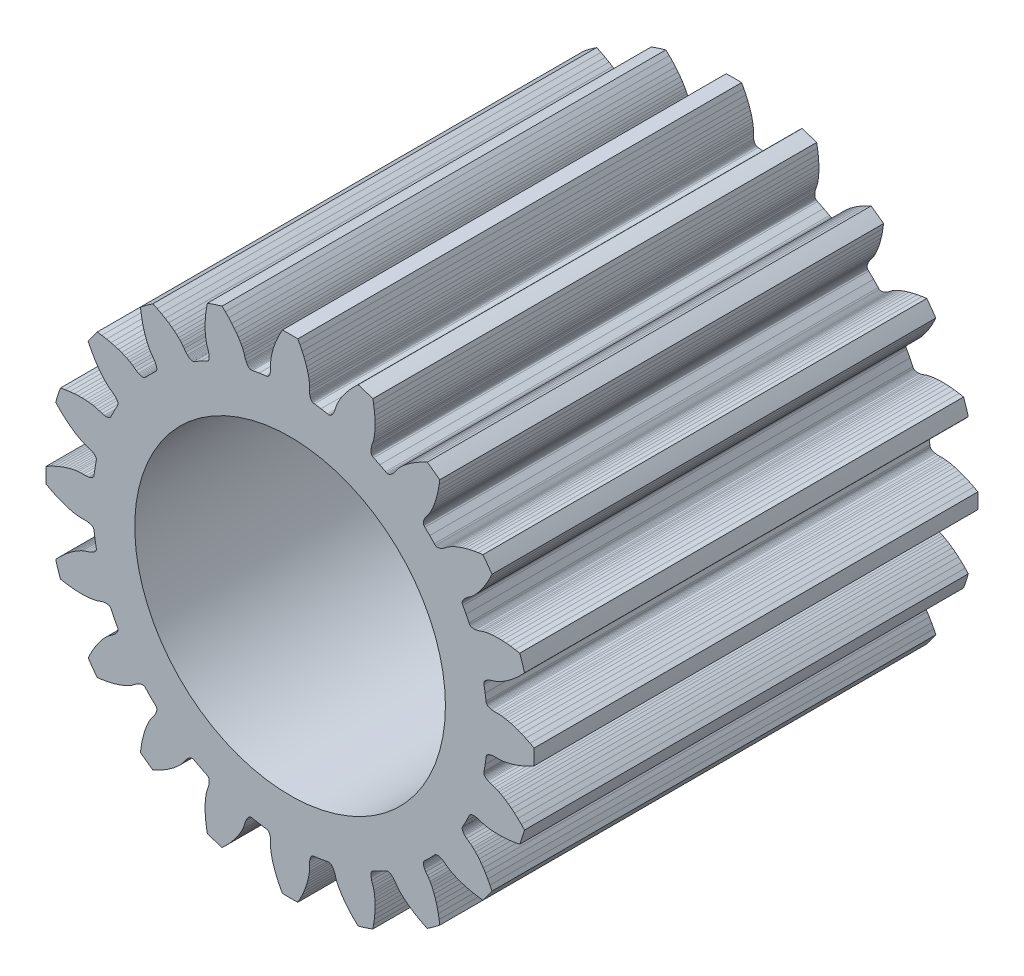
SolidWorks part; units mm, degrees
ref_plane "Front Plane" through (0, 0, 0) normal (0, 0, 1) x (1, 0, 0)
ref_plane "Top Plane" through (0, 0, 0) normal (0, 1, 0) x (1, 0, 0)
ref_plane "Right Plane" through (0, 0, 0) normal (1, 0, 0) x (0, 0, -1)
sketch "Model" plane through (0, 0, 0) normal (0, 0, 1) x (1, 0, 0)
  line L0 (5.2099, 1.4578) -> (5.132, 1.3822)
  line L1 (5.132, 1.3822) -> (5.057, 1.3153)
  line L2 (5.057, 1.3153) -> (4.9867, 1.2576)
  line L3 (4.9867, 1.2576) -> (4.9201, 1.2074)
  line L4 (4.9201, 1.2074) -> (4.8577, 1.1645)
  line L5 (4.8577, 1.1645) -> (4.8024, 1.1297)
  line L6 (4.8024, 1.1297) -> (4.75, 1.0997)
  line L7 (4.75, 1.0997) -> (4.7053, 1.0765)
  line L8 (4.7053, 1.0765) -> (4.6677, 1.059)
  line L9 (4.6677, 1.059) -> (4.6119, 1.0369)
  line L10 (4.6119, 1.0369) -> (4.5666, 1.0239)
  line L11 (4.5666, 1.0239) -> (4.5088, 1.0051)
  line L12 (4.5088, 1.0051) -> (4.4605, 0.9836)
  line L13 (4.4605, 0.9836) -> (4.4401, 0.9721)
  line L14 (4.4401, 0.9721) -> (4.422, 0.9602)
  line L15 (4.422, 0.9602) -> (4.4064, 0.948)
  line L16 (4.4064, 0.948) -> (4.3933, 0.9357)
  line L17 (4.3933, 0.9357) -> (4.3826, 0.9232)
  line L18 (4.3826, 0.9232) -> (4.3743, 0.9108)
  line L19 (4.3743, 0.9108) -> (4.3685, 0.8984)
  line L20 (4.3685, 0.8984) -> (4.3651, 0.8863)
  line L21 (4.3651, 0.8863) -> (4.3641, 0.8744)
  line L22 (4.3641, 0.8744) -> (4.3691, 0.845)
  line L23 (4.3691, 0.845) -> (4.3952, 0.6961)
  line L24 (4.3952, 0.6961) -> (4.4163, 0.5465)
  line L25 (4.4163, 0.5465) -> (4.4207, 0.517)
  line L26 (4.4207, 0.517) -> (4.4253, 0.506)
  line L27 (4.4253, 0.506) -> (4.4323, 0.4955)
  line L28 (4.4323, 0.4955) -> (4.4417, 0.4855)
  line L29 (4.4417, 0.4855) -> (4.4534, 0.4763)
  line L30 (4.4534, 0.4763) -> (4.4674, 0.4677)
  line L31 (4.4674, 0.4677) -> (4.4837, 0.46)
  line L32 (4.4837, 0.46) -> (4.5023, 0.4533)
  line L33 (4.5023, 0.4533) -> (4.5231, 0.4475)
  line L34 (4.5231, 0.4475) -> (4.5462, 0.4429)
  line L35 (4.5462, 0.4429) -> (4.5987, 0.4374)
  line L36 (4.5987, 0.4374) -> (4.6595, 0.4373)
  line L37 (4.6595, 0.4373) -> (4.7066, 0.439)
  line L38 (4.7066, 0.439) -> (4.7665, 0.4352)
  line L39 (4.7665, 0.4352) -> (4.8076, 0.4302)
  line L40 (4.8076, 0.4302) -> (4.8574, 0.422)
  line L41 (4.8574, 0.422) -> (4.9164, 0.4096)
  line L42 (4.9164, 0.4096) -> (4.9797, 0.3936)
  line L43 (4.9797, 0.3936) -> (5.0524, 0.372)
  line L44 (5.0524, 0.372) -> (5.1313, 0.3449)
  line L45 (5.1313, 0.3449) -> (5.2159, 0.3118)
  line L46 (5.2159, 0.3118) -> (5.308, 0.2713)
  line L47 (5.308, 0.2713) -> (5.4054, 0.2235)
  line L48 (5.4054, 0.2235) -> (5.4973, 0.1736)
  line L49 (5.4973, -0.1736) -> (5.4054, -0.2235)
  line L50 (5.4054, -0.2235) -> (5.308, -0.2713)
  line L51 (5.308, -0.2713) -> (5.2159, -0.3118)
  line L52 (5.2159, -0.3118) -> (5.1313, -0.3449)
  line L53 (5.1313, -0.3449) -> (5.0524, -0.372)
  line L54 (5.0524, -0.372) -> (4.9797, -0.3936)
  line L55 (4.9797, -0.3936) -> (4.9164, -0.4096)
  line L56 (4.9164, -0.4096) -> (4.8574, -0.422)
  line L57 (4.8574, -0.422) -> (4.8076, -0.4302)
  line L58 (4.8076, -0.4302) -> (4.7665, -0.4352)
  line L59 (4.7665, -0.4352) -> (4.7066, -0.439)
  line L60 (4.7066, -0.439) -> (4.6595, -0.4373)
  line L61 (4.6595, -0.4373) -> (4.5987, -0.4374)
  line L62 (4.5987, -0.4374) -> (4.5462, -0.4429)
  line L63 (4.5462, -0.4429) -> (4.5231, -0.4475)
  line L64 (4.5231, -0.4475) -> (4.5023, -0.4533)
  line L65 (4.5023, -0.4533) -> (4.4837, -0.46)
  line L66 (4.4837, -0.46) -> (4.4674, -0.4677)
  line L67 (4.4674, -0.4677) -> (4.4534, -0.4763)
  line L68 (4.4534, -0.4763) -> (4.4417, -0.4855)
  line L69 (4.4417, -0.4855) -> (4.4323, -0.4955)
  line L70 (4.4323, -0.4955) -> (4.4253, -0.506)
  line L71 (4.4253, -0.506) -> (4.4207, -0.517)
  line L72 (4.4207, -0.517) -> (4.4163, -0.5465)
  line L73 (4.4163, -0.5465) -> (4.3952, -0.6961)
  line L74 (4.3952, -0.6961) -> (4.3691, -0.845)
  line L75 (4.3691, -0.845) -> (4.3641, -0.8744)
  line L76 (4.3641, -0.8744) -> (4.3651, -0.8863)
  line L77 (4.3651, -0.8863) -> (4.3685, -0.8984)
  line L78 (4.3685, -0.8984) -> (4.3743, -0.9108)
  line L79 (4.3743, -0.9108) -> (4.3826, -0.9232)
  line L80 (4.3826, -0.9232) -> (4.3933, -0.9357)
  line L81 (4.3933, -0.9357) -> (4.4064, -0.948)
  line L82 (4.4064, -0.948) -> (4.422, -0.9602)
  line L83 (4.422, -0.9602) -> (4.4401, -0.9721)
  line L84 (4.4401, -0.9721) -> (4.4605, -0.9836)
  line L85 (4.4605, -0.9836) -> (4.5088, -1.0051)
  line L86 (4.5088, -1.0051) -> (4.5666, -1.0239)
  line L87 (4.5666, -1.0239) -> (4.6119, -1.0369)
  line L88 (4.6119, -1.0369) -> (4.6677, -1.059)
  line L89 (4.6677, -1.059) -> (4.7053, -1.0765)
  line L90 (4.7053, -1.0765) -> (4.75, -1.0997)
  line L91 (4.75, -1.0997) -> (4.8024, -1.1297)
  line L92 (4.8024, -1.1297) -> (4.8577, -1.1645)
  line L93 (4.8577, -1.1645) -> (4.9201, -1.2074)
  line L94 (4.9201, -1.2074) -> (4.9867, -1.2576)
  line L95 (4.9867, -1.2576) -> (5.057, -1.3153)
  line L96 (5.057, -1.3153) -> (5.132, -1.3822)
  line L97 (5.132, -1.3822) -> (5.2099, -1.4578)
  line L98 (5.2099, -1.4578) -> (5.2818, -1.5336)
  line L99 (5.1745, -1.8639) -> (5.0718, -1.8829)
  line L100 (5.0718, -1.8829) -> (4.9643, -1.8983)
  line L101 (4.9643, -1.8983) -> (4.8643, -1.9084)
  line L102 (4.8643, -1.9084) -> (4.7736, -1.9137)
  line L103 (4.7736, -1.9137) -> (4.6901, -1.9151)
  line L104 (4.6901, -1.9151) -> (4.6144, -1.9132)
  line L105 (4.6144, -1.9132) -> (4.5492, -1.9088)
  line L106 (4.5492, -1.9088) -> (4.4893, -1.9023)
  line L107 (4.4893, -1.9023) -> (4.4394, -1.8947)
  line L108 (4.4394, -1.8947) -> (4.3987, -1.8868)
  line L109 (4.3987, -1.8868) -> (4.3406, -1.8719)
  line L110 (4.3406, -1.8719) -> (4.2963, -1.8558)
  line L111 (4.2963, -1.8558) -> (4.2385, -1.837)
  line L112 (4.2385, -1.837) -> (4.1868, -1.8261)
  line L113 (4.1868, -1.8261) -> (4.1635, -1.8234)
  line L114 (4.1635, -1.8234) -> (4.1419, -1.8224)
  line L115 (4.1419, -1.8224) -> (4.1221, -1.8231)
  line L116 (4.1221, -1.8231) -> (4.1042, -1.8253)
  line L117 (4.1042, -1.8253) -> (4.0882, -1.8291)
  line L118 (4.0882, -1.8291) -> (4.0742, -1.8343)
  line L119 (4.0742, -1.8343) -> (4.0623, -1.8409)
  line L120 (4.0623, -1.8409) -> (4.0524, -1.8487)
  line L121 (4.0524, -1.8487) -> (4.0446, -1.8577)
  line L122 (4.0446, -1.8577) -> (4.0313, -1.8845)
  line L123 (4.0313, -1.8845) -> (3.965, -2.0203)
  line L124 (3.965, -2.0203) -> (3.8941, -2.1537)
  line L125 (3.8941, -2.1537) -> (3.8803, -2.1802)
  line L126 (3.8803, -2.1802) -> (3.8776, -2.1918)
  line L127 (3.8776, -2.1918) -> (3.8771, -2.2044)
  line L128 (3.8771, -2.2044) -> (3.8788, -2.2179)
  line L129 (3.8788, -2.2179) -> (3.8828, -2.2323)
  line L130 (3.8828, -2.2323) -> (3.8891, -2.2475)
  line L131 (3.8891, -2.2475) -> (3.8978, -2.2633)
  line L132 (3.8978, -2.2633) -> (3.9089, -2.2797)
  line L133 (3.9089, -2.2797) -> (3.9224, -2.2966)
  line L134 (3.9224, -2.2966) -> (3.9383, -2.3139)
  line L135 (3.9383, -2.3139) -> (3.9775, -2.3492)
  line L136 (3.9775, -2.3492) -> (4.0267, -2.385)
  line L137 (4.0267, -2.385) -> (4.0658, -2.4113)
  line L138 (4.0658, -2.4113) -> (4.112, -2.4496)
  line L139 (4.112, -2.4496) -> (4.1423, -2.4778)
  line L140 (4.1423, -2.4778) -> (4.1777, -2.5137)
  line L141 (4.1777, -2.5137) -> (4.2182, -2.5584)
  line L142 (4.2182, -2.5584) -> (4.2601, -2.6086)
  line L143 (4.2601, -2.6086) -> (4.3061, -2.6687)
  line L144 (4.3061, -2.6687) -> (4.354, -2.7371)
  line L145 (4.354, -2.7371) -> (4.4031, -2.8136)
  line L146 (4.4031, -2.8136) -> (4.4537, -2.9004)
  line L147 (4.4537, -2.9004) -> (4.5044, -2.9964)
  line L148 (4.5044, -2.9964) -> (4.5494, -3.0907)
  line L149 (4.3453, -3.3717) -> (4.2417, -3.358)
  line L150 (4.2417, -3.358) -> (4.1348, -3.3394)
  line L151 (4.1348, -3.3394) -> (4.0365, -3.3181)
  line L152 (4.0365, -3.3181) -> (3.9486, -3.2951)
  line L153 (3.9486, -3.2951) -> (3.8688, -3.2707)
  line L154 (3.8688, -3.2707) -> (3.7973, -3.2455)
  line L155 (3.7973, -3.2455) -> (3.7367, -3.2212)
  line L156 (3.7367, -3.2212) -> (3.6817, -3.1965)
  line L157 (3.6817, -3.1965) -> (3.6366, -3.1739)
  line L158 (3.6366, -3.1739) -> (3.6004, -3.1538)
  line L159 (3.6004, -3.1538) -> (3.5497, -3.1216)
  line L160 (3.5497, -3.1216) -> (3.5126, -3.0926)
  line L161 (3.5126, -3.0926) -> (3.4634, -3.0569)
  line L162 (3.4634, -3.0569) -> (3.4176, -3.0305)
  line L163 (3.4176, -3.0305) -> (3.3963, -3.0207)
  line L164 (3.3963, -3.0207) -> (3.376, -3.0131)
  line L165 (3.376, -3.0131) -> (3.357, -3.0076)
  line L166 (3.357, -3.0076) -> (3.3393, -3.0043)
  line L167 (3.3393, -3.0043) -> (3.3229, -3.0029)
  line L168 (3.3229, -3.0029) -> (3.308, -3.0036)
  line L169 (3.308, -3.0036) -> (3.2946, -3.0061)
  line L170 (3.2946, -3.0061) -> (3.2828, -3.0105)
  line L171 (3.2828, -3.0105) -> (3.2726, -3.0167)
  line L172 (3.2726, -3.0167) -> (3.2517, -3.038)
  line L173 (3.2517, -3.038) -> (3.1466, -3.1466)
  line L174 (3.1466, -3.1466) -> (3.038, -3.2517)
  line L175 (3.038, -3.2517) -> (3.0167, -3.2726)
  line L176 (3.0167, -3.2726) -> (3.0105, -3.2828)
  line L177 (3.0105, -3.2828) -> (3.0061, -3.2946)
  line L178 (3.0061, -3.2946) -> (3.0036, -3.308)
  line L179 (3.0036, -3.308) -> (3.0029, -3.3229)
  line L180 (3.0029, -3.3229) -> (3.0043, -3.3393)
  line L181 (3.0043, -3.3393) -> (3.0076, -3.357)
  line L182 (3.0076, -3.357) -> (3.0131, -3.376)
  line L183 (3.0131, -3.376) -> (3.0207, -3.3963)
  line L184 (3.0207, -3.3963) -> (3.0305, -3.4176)
  line L185 (3.0305, -3.4176) -> (3.0569, -3.4634)
  line L186 (3.0569, -3.4634) -> (3.0926, -3.5126)
  line L187 (3.0926, -3.5126) -> (3.1216, -3.5497)
  line L188 (3.1216, -3.5497) -> (3.1538, -3.6004)
  line L189 (3.1538, -3.6004) -> (3.1739, -3.6366)
  line L190 (3.1739, -3.6366) -> (3.1965, -3.6817)
  line L191 (3.1965, -3.6817) -> (3.2212, -3.7367)
  line L192 (3.2212, -3.7367) -> (3.2455, -3.7973)
  line L193 (3.2455, -3.7973) -> (3.2707, -3.8688)
  line L194 (3.2707, -3.8688) -> (3.2951, -3.9486)
  line L195 (3.2951, -3.9486) -> (3.3181, -4.0365)
  line L196 (3.3181, -4.0365) -> (3.3394, -4.1348)
  line L197 (3.3394, -4.1348) -> (3.358, -4.2417)
  line L198 (3.358, -4.2417) -> (3.3717, -4.3453)
  line L199 (3.0907, -4.5494) -> (2.9964, -4.5044)
  line L200 (2.9964, -4.5044) -> (2.9004, -4.4537)
  line L201 (2.9004, -4.4537) -> (2.8136, -4.4031)
  line L202 (2.8136, -4.4031) -> (2.7371, -4.354)
  line L203 (2.7371, -4.354) -> (2.6687, -4.3061)
  line L204 (2.6687, -4.3061) -> (2.6086, -4.2601)
  line L205 (2.6086, -4.2601) -> (2.5584, -4.2182)
  line L206 (2.5584, -4.2182) -> (2.5137, -4.1777)
  line L207 (2.5137, -4.1777) -> (2.4778, -4.1423)
  line L208 (2.4778, -4.1423) -> (2.4496, -4.112)
  line L209 (2.4496, -4.112) -> (2.4113, -4.0658)
  line L210 (2.4113, -4.0658) -> (2.385, -4.0267)
  line L211 (2.385, -4.0267) -> (2.3492, -3.9775)
  line L212 (2.3492, -3.9775) -> (2.3139, -3.9383)
  line L213 (2.3139, -3.9383) -> (2.2966, -3.9224)
  line L214 (2.2966, -3.9224) -> (2.2797, -3.9089)
  line L215 (2.2797, -3.9089) -> (2.2633, -3.8978)
  line L216 (2.2633, -3.8978) -> (2.2475, -3.8891)
  line L217 (2.2475, -3.8891) -> (2.2323, -3.8828)
  line L218 (2.2323, -3.8828) -> (2.2179, -3.8788)
  line L219 (2.2179, -3.8788) -> (2.2044, -3.8771)
  line L220 (2.2044, -3.8771) -> (2.1918, -3.8776)
  line L221 (2.1918, -3.8776) -> (2.1802, -3.8803)
  line L222 (2.1802, -3.8803) -> (2.1537, -3.8941)
  line L223 (2.1537, -3.8941) -> (2.0203, -3.965)
  line L224 (2.0203, -3.965) -> (1.8845, -4.0313)
  line L225 (1.8845, -4.0313) -> (1.8577, -4.0446)
  line L226 (1.8577, -4.0446) -> (1.8487, -4.0524)
  line L227 (1.8487, -4.0524) -> (1.8409, -4.0623)
  line L228 (1.8409, -4.0623) -> (1.8343, -4.0742)
  line L229 (1.8343, -4.0742) -> (1.8291, -4.0882)
  line L230 (1.8291, -4.0882) -> (1.8253, -4.1042)
  line L231 (1.8253, -4.1042) -> (1.8231, -4.1221)
  line L232 (1.8231, -4.1221) -> (1.8224, -4.1419)
  line L233 (1.8224, -4.1419) -> (1.8234, -4.1635)
  line L234 (1.8234, -4.1635) -> (1.8261, -4.1868)
  line L235 (1.8261, -4.1868) -> (1.837, -4.2385)
  line L236 (1.837, -4.2385) -> (1.8558, -4.2963)
  line L237 (1.8558, -4.2963) -> (1.8719, -4.3406)
  line L238 (1.8719, -4.3406) -> (1.8868, -4.3987)
  line L239 (1.8868, -4.3987) -> (1.8947, -4.4394)
  line L240 (1.8947, -4.4394) -> (1.9023, -4.4893)
  line L241 (1.9023, -4.4893) -> (1.9088, -4.5492)
  line L242 (1.9088, -4.5492) -> (1.9132, -4.6144)
  line L243 (1.9132, -4.6144) -> (1.9151, -4.6901)
  line L244 (1.9151, -4.6901) -> (1.9137, -4.7736)
  line L245 (1.9137, -4.7736) -> (1.9084, -4.8643)
  line L246 (1.9084, -4.8643) -> (1.8983, -4.9643)
  line L247 (1.8983, -4.9643) -> (1.8829, -5.0718)
  line L248 (1.8829, -5.0718) -> (1.8639, -5.1745)
  line L249 (1.5336, -5.2818) -> (1.4578, -5.2099)
  line L250 (1.4578, -5.2099) -> (1.3822, -5.132)
  line L251 (1.3822, -5.132) -> (1.3153, -5.057)
  line L252 (1.3153, -5.057) -> (1.2576, -4.9867)
  line L253 (1.2576, -4.9867) -> (1.2074, -4.9201)
  line L254 (1.2074, -4.9201) -> (1.1645, -4.8577)
  line L255 (1.1645, -4.8577) -> (1.1297, -4.8024)
  line L256 (1.1297, -4.8024) -> (1.0997, -4.75)
  line L257 (1.0997, -4.75) -> (1.0765, -4.7053)
  line L258 (1.0765, -4.7053) -> (1.059, -4.6677)
  line L259 (1.059, -4.6677) -> (1.0369, -4.6119)
  line L260 (1.0369, -4.6119) -> (1.0239, -4.5666)
  line L261 (1.0239, -4.5666) -> (1.0051, -4.5088)
  line L262 (1.0051, -4.5088) -> (0.9836, -4.4605)
  line L263 (0.9836, -4.4605) -> (0.9721, -4.4401)
  line L264 (0.9721, -4.4401) -> (0.9602, -4.422)
  line L265 (0.9602, -4.422) -> (0.948, -4.4064)
  line L266 (0.948, -4.4064) -> (0.9357, -4.3933)
  line L267 (0.9357, -4.3933) -> (0.9232, -4.3826)
  line L268 (0.9232, -4.3826) -> (0.9108, -4.3743)
  line L269 (0.9108, -4.3743) -> (0.8984, -4.3685)
  line L270 (0.8984, -4.3685) -> (0.8863, -4.3651)
  line L271 (0.8863, -4.3651) -> (0.8744, -4.3641)
  line L272 (0.8744, -4.3641) -> (0.845, -4.3691)
  line L273 (0.845, -4.3691) -> (0.6961, -4.3952)
  line L274 (0.6961, -4.3952) -> (0.5465, -4.4163)
  line L275 (0.5465, -4.4163) -> (0.517, -4.4207)
  line L276 (0.517, -4.4207) -> (0.506, -4.4253)
  line L277 (0.506, -4.4253) -> (0.4955, -4.4323)
  line L278 (0.4955, -4.4323) -> (0.4855, -4.4417)
  line L279 (0.4855, -4.4417) -> (0.4763, -4.4534)
  line L280 (0.4763, -4.4534) -> (0.4677, -4.4674)
  line L281 (0.4677, -4.4674) -> (0.46, -4.4837)
  line L282 (0.46, -4.4837) -> (0.4533, -4.5023)
  line L283 (0.4533, -4.5023) -> (0.4475, -4.5231)
  line L284 (0.4475, -4.5231) -> (0.4429, -4.5462)
  line L285 (0.4429, -4.5462) -> (0.4374, -4.5987)
  line L286 (0.4374, -4.5987) -> (0.4373, -4.6595)
  line L287 (0.4373, -4.6595) -> (0.439, -4.7066)
  line L288 (0.439, -4.7066) -> (0.4352, -4.7665)
  line L289 (0.4352, -4.7665) -> (0.4302, -4.8076)
  line L290 (0.4302, -4.8076) -> (0.422, -4.8574)
  line L291 (0.422, -4.8574) -> (0.4096, -4.9164)
  line L292 (0.4096, -4.9164) -> (0.3936, -4.9797)
  line L293 (0.3936, -4.9797) -> (0.372, -5.0524)
  line L294 (0.372, -5.0524) -> (0.3449, -5.1313)
  line L295 (0.3449, -5.1313) -> (0.3118, -5.2159)
  line L296 (0.3118, -5.2159) -> (0.2713, -5.308)
  line L297 (0.2713, -5.308) -> (0.2235, -5.4054)
  line L298 (0.2235, -5.4054) -> (0.1736, -5.4973)
  line L299 (-0.1736, -5.4973) -> (-0.2235, -5.4054)
  line L300 (-0.2235, -5.4054) -> (-0.2713, -5.308)
  line L301 (-0.2713, -5.308) -> (-0.3118, -5.2159)
  line L302 (-0.3118, -5.2159) -> (-0.3449, -5.1313)
  line L303 (-0.3449, -5.1313) -> (-0.372, -5.0524)
  line L304 (-0.372, -5.0524) -> (-0.3936, -4.9797)
  line L305 (-0.3936, -4.9797) -> (-0.4096, -4.9164)
  line L306 (-0.4096, -4.9164) -> (-0.422, -4.8574)
  line L307 (-0.422, -4.8574) -> (-0.4302, -4.8076)
  line L308 (-0.4302, -4.8076) -> (-0.4352, -4.7665)
  line L309 (-0.4352, -4.7665) -> (-0.439, -4.7066)
  line L310 (-0.439, -4.7066) -> (-0.4373, -4.6595)
  line L311 (-0.4373, -4.6595) -> (-0.4374, -4.5987)
  line L312 (-0.4374, -4.5987) -> (-0.4429, -4.5462)
  line L313 (-0.4429, -4.5462) -> (-0.4475, -4.5231)
  line L314 (-0.4475, -4.5231) -> (-0.4533, -4.5023)
  line L315 (-0.4533, -4.5023) -> (-0.46, -4.4837)
  line L316 (-0.46, -4.4837) -> (-0.4677, -4.4674)
  line L317 (-0.4677, -4.4674) -> (-0.4763, -4.4534)
  line L318 (-0.4763, -4.4534) -> (-0.4855, -4.4417)
  line L319 (-0.4855, -4.4417) -> (-0.4955, -4.4323)
  line L320 (-0.4955, -4.4323) -> (-0.506, -4.4253)
  line L321 (-0.506, -4.4253) -> (-0.517, -4.4207)
  line L322 (-0.517, -4.4207) -> (-0.5465, -4.4163)
  line L323 (-0.5465, -4.4163) -> (-0.6961, -4.3952)
  line L324 (-0.6961, -4.3952) -> (-0.845, -4.3691)
  line L325 (-0.845, -4.3691) -> (-0.8744, -4.3641)
  line L326 (-0.8744, -4.3641) -> (-0.8863, -4.3651)
  line L327 (-0.8863, -4.3651) -> (-0.8984, -4.3685)
  line L328 (-0.8984, -4.3685) -> (-0.9108, -4.3743)
  line L329 (-0.9108, -4.3743) -> (-0.9232, -4.3826)
  line L330 (-0.9232, -4.3826) -> (-0.9357, -4.3933)
  line L331 (-0.9357, -4.3933) -> (-0.948, -4.4064)
  line L332 (-0.948, -4.4064) -> (-0.9602, -4.422)
  line L333 (-0.9602, -4.422) -> (-0.9721, -4.4401)
  line L334 (-0.9721, -4.4401) -> (-0.9836, -4.4605)
  line L335 (-0.9836, -4.4605) -> (-1.0051, -4.5088)
  line L336 (-1.0051, -4.5088) -> (-1.0239, -4.5666)
  line L337 (-1.0239, -4.5666) -> (-1.0369, -4.6119)
  line L338 (-1.0369, -4.6119) -> (-1.059, -4.6677)
  line L339 (-1.059, -4.6677) -> (-1.0765, -4.7053)
  line L340 (-1.0765, -4.7053) -> (-1.0997, -4.75)
  line L341 (-1.0997, -4.75) -> (-1.1297, -4.8024)
  line L342 (-1.1297, -4.8024) -> (-1.1645, -4.8577)
  line L343 (-1.1645, -4.8577) -> (-1.2074, -4.9201)
  line L344 (-1.2074, -4.9201) -> (-1.2576, -4.9867)
  line L345 (-1.2576, -4.9867) -> (-1.3153, -5.057)
  line L346 (-1.3153, -5.057) -> (-1.3822, -5.132)
  line L347 (-1.3822, -5.132) -> (-1.4578, -5.2099)
  line L348 (-1.4578, -5.2099) -> (-1.5336, -5.2818)
  line L349 (-1.8639, -5.1745) -> (-1.8829, -5.0718)
  line L350 (-1.8829, -5.0718) -> (-1.8983, -4.9643)
  line L351 (-1.8983, -4.9643) -> (-1.9084, -4.8643)
  line L352 (-1.9084, -4.8643) -> (-1.9137, -4.7736)
  line L353 (-1.9137, -4.7736) -> (-1.9151, -4.6901)
  line L354 (-1.9151, -4.6901) -> (-1.9132, -4.6144)
  line L355 (-1.9132, -4.6144) -> (-1.9088, -4.5492)
  line L356 (-1.9088, -4.5492) -> (-1.9023, -4.4893)
  line L357 (-1.9023, -4.4893) -> (-1.8947, -4.4394)
  line L358 (-1.8947, -4.4394) -> (-1.8868, -4.3987)
  line L359 (-1.8868, -4.3987) -> (-1.8719, -4.3406)
  line L360 (-1.8719, -4.3406) -> (-1.8558, -4.2963)
  line L361 (-1.8558, -4.2963) -> (-1.837, -4.2385)
  line L362 (-1.837, -4.2385) -> (-1.8261, -4.1868)
  line L363 (-1.8261, -4.1868) -> (-1.8234, -4.1635)
  line L364 (-1.8234, -4.1635) -> (-1.8224, -4.1419)
  line L365 (-1.8224, -4.1419) -> (-1.8231, -4.1221)
  line L366 (-1.8231, -4.1221) -> (-1.8253, -4.1042)
  line L367 (-1.8253, -4.1042) -> (-1.8291, -4.0882)
  line L368 (-1.8291, -4.0882) -> (-1.8343, -4.0742)
  line L369 (-1.8343, -4.0742) -> (-1.8409, -4.0623)
  line L370 (-1.8409, -4.0623) -> (-1.8487, -4.0524)
  line L371 (-1.8487, -4.0524) -> (-1.8577, -4.0446)
  line L372 (-1.8577, -4.0446) -> (-1.8845, -4.0313)
  line L373 (-1.8845, -4.0313) -> (-2.0203, -3.965)
  line L374 (-2.0203, -3.965) -> (-2.1537, -3.8941)
  line L375 (-2.1537, -3.8941) -> (-2.1802, -3.8803)
  line L376 (-2.1802, -3.8803) -> (-2.1918, -3.8776)
  line L377 (-2.1918, -3.8776) -> (-2.2044, -3.8771)
  line L378 (-2.2044, -3.8771) -> (-2.2179, -3.8788)
  line L379 (-2.2179, -3.8788) -> (-2.2323, -3.8828)
  line L380 (-2.2323, -3.8828) -> (-2.2475, -3.8891)
  line L381 (-2.2475, -3.8891) -> (-2.2633, -3.8978)
  line L382 (-2.2633, -3.8978) -> (-2.2797, -3.9089)
  line L383 (-2.2797, -3.9089) -> (-2.2966, -3.9224)
  line L384 (-2.2966, -3.9224) -> (-2.3139, -3.9383)
  line L385 (-2.3139, -3.9383) -> (-2.3492, -3.9775)
  line L386 (-2.3492, -3.9775) -> (-2.385, -4.0267)
  line L387 (-2.385, -4.0267) -> (-2.4113, -4.0658)
  line L388 (-2.4113, -4.0658) -> (-2.4496, -4.112)
  line L389 (-2.4496, -4.112) -> (-2.4778, -4.1423)
  line L390 (-2.4778, -4.1423) -> (-2.5137, -4.1777)
  line L391 (-2.5137, -4.1777) -> (-2.5584, -4.2182)
  line L392 (-2.5584, -4.2182) -> (-2.6086, -4.2601)
  line L393 (-2.6086, -4.2601) -> (-2.6687, -4.3061)
  line L394 (-2.6687, -4.3061) -> (-2.7371, -4.354)
  line L395 (-2.7371, -4.354) -> (-2.8136, -4.4031)
  line L396 (-2.8136, -4.4031) -> (-2.9004, -4.4537)
  line L397 (-2.9004, -4.4537) -> (-2.9964, -4.5044)
  line L398 (-2.9964, -4.5044) -> (-3.0907, -4.5494)
  line L399 (-3.3717, -4.3453) -> (-3.358, -4.2417)
  line L400 (-3.358, -4.2417) -> (-3.3394, -4.1348)
  line L401 (-3.3394, -4.1348) -> (-3.3181, -4.0365)
  line L402 (-3.3181, -4.0365) -> (-3.2951, -3.9486)
  line L403 (-3.2951, -3.9486) -> (-3.2707, -3.8688)
  line L404 (-3.2707, -3.8688) -> (-3.2455, -3.7973)
  line L405 (-3.2455, -3.7973) -> (-3.2212, -3.7367)
  line L406 (-3.2212, -3.7367) -> (-3.1965, -3.6817)
  line L407 (-3.1965, -3.6817) -> (-3.1739, -3.6366)
  line L408 (-3.1739, -3.6366) -> (-3.1538, -3.6004)
  line L409 (-3.1538, -3.6004) -> (-3.1216, -3.5497)
  line L410 (-3.1216, -3.5497) -> (-3.0926, -3.5126)
  line L411 (-3.0926, -3.5126) -> (-3.0569, -3.4634)
  line L412 (-3.0569, -3.4634) -> (-3.0305, -3.4176)
  line L413 (-3.0305, -3.4176) -> (-3.0207, -3.3963)
  line L414 (-3.0207, -3.3963) -> (-3.0131, -3.376)
  line L415 (-3.0131, -3.376) -> (-3.0076, -3.357)
  line L416 (-3.0076, -3.357) -> (-3.0043, -3.3393)
  line L417 (-3.0043, -3.3393) -> (-3.0029, -3.3229)
  line L418 (-3.0029, -3.3229) -> (-3.0036, -3.308)
  line L419 (-3.0036, -3.308) -> (-3.0061, -3.2946)
  line L420 (-3.0061, -3.2946) -> (-3.0105, -3.2828)
  line L421 (-3.0105, -3.2828) -> (-3.0167, -3.2726)
  line L422 (-3.0167, -3.2726) -> (-3.038, -3.2517)
  line L423 (-3.038, -3.2517) -> (-3.1466, -3.1466)
  line L424 (-3.1466, -3.1466) -> (-3.2517, -3.038)
  line L425 (-3.2517, -3.038) -> (-3.2726, -3.0167)
  line L426 (-3.2726, -3.0167) -> (-3.2828, -3.0105)
  line L427 (-3.2828, -3.0105) -> (-3.2946, -3.0061)
  line L428 (-3.2946, -3.0061) -> (-3.308, -3.0036)
  line L429 (-3.308, -3.0036) -> (-3.3229, -3.0029)
  line L430 (-3.3229, -3.0029) -> (-3.3393, -3.0043)
  line L431 (-3.3393, -3.0043) -> (-3.357, -3.0076)
  line L432 (-3.357, -3.0076) -> (-3.376, -3.0131)
  line L433 (-3.376, -3.0131) -> (-3.3963, -3.0207)
  line L434 (-3.3963, -3.0207) -> (-3.4176, -3.0305)
  line L435 (-3.4176, -3.0305) -> (-3.4634, -3.0569)
  line L436 (-3.4634, -3.0569) -> (-3.5126, -3.0926)
  line L437 (-3.5126, -3.0926) -> (-3.5497, -3.1216)
  line L438 (-3.5497, -3.1216) -> (-3.6004, -3.1538)
  line L439 (-3.6004, -3.1538) -> (-3.6366, -3.1739)
  line L440 (-3.6366, -3.1739) -> (-3.6817, -3.1965)
  line L441 (-3.6817, -3.1965) -> (-3.7367, -3.2212)
  line L442 (-3.7367, -3.2212) -> (-3.7973, -3.2455)
  line L443 (-3.7973, -3.2455) -> (-3.8688, -3.2707)
  line L444 (-3.8688, -3.2707) -> (-3.9486, -3.2951)
  line L445 (-3.9486, -3.2951) -> (-4.0365, -3.3181)
  line L446 (-4.0365, -3.3181) -> (-4.1348, -3.3394)
  line L447 (-4.1348, -3.3394) -> (-4.2417, -3.358)
  line L448 (-4.2417, -3.358) -> (-4.3453, -3.3717)
  line L449 (-4.5494, -3.0907) -> (-4.5044, -2.9964)
  line L450 (-4.5044, -2.9964) -> (-4.4537, -2.9004)
  line L451 (-4.4537, -2.9004) -> (-4.4031, -2.8136)
  line L452 (-4.4031, -2.8136) -> (-4.354, -2.7371)
  line L453 (-4.354, -2.7371) -> (-4.3061, -2.6687)
  line L454 (-4.3061, -2.6687) -> (-4.2601, -2.6086)
  line L455 (-4.2601, -2.6086) -> (-4.2182, -2.5584)
  line L456 (-4.2182, -2.5584) -> (-4.1777, -2.5137)
  line L457 (-4.1777, -2.5137) -> (-4.1423, -2.4778)
  line L458 (-4.1423, -2.4778) -> (-4.112, -2.4496)
  line L459 (-4.112, -2.4496) -> (-4.0658, -2.4113)
  line L460 (-4.0658, -2.4113) -> (-4.0267, -2.385)
  line L461 (-4.0267, -2.385) -> (-3.9775, -2.3492)
  line L462 (-3.9775, -2.3492) -> (-3.9383, -2.3139)
  line L463 (-3.9383, -2.3139) -> (-3.9224, -2.2966)
  line L464 (-3.9224, -2.2966) -> (-3.9089, -2.2797)
  line L465 (-3.9089, -2.2797) -> (-3.8978, -2.2633)
  line L466 (-3.8978, -2.2633) -> (-3.8891, -2.2475)
  line L467 (-3.8891, -2.2475) -> (-3.8828, -2.2323)
  line L468 (-3.8828, -2.2323) -> (-3.8788, -2.2179)
  line L469 (-3.8788, -2.2179) -> (-3.8771, -2.2044)
  line L470 (-3.8771, -2.2044) -> (-3.8776, -2.1918)
  line L471 (-3.8776, -2.1918) -> (-3.8803, -2.1802)
  line L472 (-3.8803, -2.1802) -> (-3.8941, -2.1537)
  line L473 (-3.8941, -2.1537) -> (-3.965, -2.0203)
  line L474 (-3.965, -2.0203) -> (-4.0313, -1.8845)
  line L475 (-4.0313, -1.8845) -> (-4.0446, -1.8577)
  line L476 (-4.0446, -1.8577) -> (-4.0524, -1.8487)
  line L477 (-4.0524, -1.8487) -> (-4.0623, -1.8409)
  line L478 (-4.0623, -1.8409) -> (-4.0742, -1.8343)
  line L479 (-4.0742, -1.8343) -> (-4.0882, -1.8291)
  line L480 (-4.0882, -1.8291) -> (-4.1042, -1.8253)
  line L481 (-4.1042, -1.8253) -> (-4.1221, -1.8231)
  line L482 (-4.1221, -1.8231) -> (-4.1419, -1.8224)
  line L483 (-4.1419, -1.8224) -> (-4.1635, -1.8234)
  line L484 (-4.1635, -1.8234) -> (-4.1868, -1.8261)
  line L485 (-4.1868, -1.8261) -> (-4.2385, -1.837)
  line L486 (-4.2385, -1.837) -> (-4.2963, -1.8558)
  line L487 (-4.2963, -1.8558) -> (-4.3406, -1.8719)
  line L488 (-4.3406, -1.8719) -> (-4.3987, -1.8868)
  line L489 (-4.3987, -1.8868) -> (-4.4394, -1.8947)
  line L490 (-4.4394, -1.8947) -> (-4.4893, -1.9023)
  line L491 (-4.4893, -1.9023) -> (-4.5492, -1.9088)
  line L492 (-4.5492, -1.9088) -> (-4.6144, -1.9132)
  line L493 (-4.6144, -1.9132) -> (-4.6901, -1.9151)
  line L494 (-4.6901, -1.9151) -> (-4.7736, -1.9137)
  line L495 (-4.7736, -1.9137) -> (-4.8643, -1.9084)
  line L496 (-4.8643, -1.9084) -> (-4.9643, -1.8983)
  line L497 (-4.9643, -1.8983) -> (-5.0718, -1.8829)
  line L498 (-5.0718, -1.8829) -> (-5.1745, -1.8639)
  line L499 (-5.2818, -1.5336) -> (-5.2099, -1.4578)
  line L500 (-5.2099, -1.4578) -> (-5.132, -1.3822)
  line L501 (-5.132, -1.3822) -> (-5.057, -1.3153)
  line L502 (-5.057, -1.3153) -> (-4.9867, -1.2576)
  line L503 (-4.9867, -1.2576) -> (-4.9201, -1.2074)
  line L504 (-4.9201, -1.2074) -> (-4.8577, -1.1645)
  line L505 (-4.8577, -1.1645) -> (-4.8024, -1.1297)
  line L506 (-4.8024, -1.1297) -> (-4.75, -1.0997)
  line L507 (-4.75, -1.0997) -> (-4.7053, -1.0765)
  line L508 (-4.7053, -1.0765) -> (-4.6677, -1.059)
  line L509 (-4.6677, -1.059) -> (-4.6119, -1.0369)
  line L510 (-4.6119, -1.0369) -> (-4.5666, -1.0239)
  line L511 (-4.5666, -1.0239) -> (-4.5088, -1.0051)
  line L512 (-4.5088, -1.0051) -> (-4.4605, -0.9836)
  line L513 (-4.4605, -0.9836) -> (-4.4401, -0.9721)
  line L514 (-4.4401, -0.9721) -> (-4.422, -0.9602)
  line L515 (-4.422, -0.9602) -> (-4.4064, -0.948)
  line L516 (-4.4064, -0.948) -> (-4.3933, -0.9357)
  line L517 (-4.3933, -0.9357) -> (-4.3826, -0.9232)
  line L518 (-4.3826, -0.9232) -> (-4.3743, -0.9108)
  line L519 (-4.3743, -0.9108) -> (-4.3685, -0.8984)
  line L520 (-4.3685, -0.8984) -> (-4.3651, -0.8863)
  line L521 (-4.3651, -0.8863) -> (-4.3641, -0.8744)
  line L522 (-4.3641, -0.8744) -> (-4.3691, -0.845)
  line L523 (-4.3691, -0.845) -> (-4.3952, -0.6961)
  line L524 (-4.3952, -0.6961) -> (-4.4163, -0.5465)
  line L525 (-4.4163, -0.5465) -> (-4.4207, -0.517)
  line L526 (-4.4207, -0.517) -> (-4.4253, -0.506)
  line L527 (-4.4253, -0.506) -> (-4.4323, -0.4955)
  line L528 (-4.4323, -0.4955) -> (-4.4417, -0.4855)
  line L529 (-4.4417, -0.4855) -> (-4.4534, -0.4763)
  line L530 (-4.4534, -0.4763) -> (-4.4674, -0.4677)
  line L531 (-4.4674, -0.4677) -> (-4.4837, -0.46)
  line L532 (-4.4837, -0.46) -> (-4.5023, -0.4533)
  line L533 (-4.5023, -0.4533) -> (-4.5231, -0.4475)
  line L534 (-4.5231, -0.4475) -> (-4.5462, -0.4429)
  line L535 (-4.5462, -0.4429) -> (-4.5987, -0.4374)
  line L536 (-4.5987, -0.4374) -> (-4.6595, -0.4373)
  line L537 (-4.6595, -0.4373) -> (-4.7066, -0.439)
  line L538 (-4.7066, -0.439) -> (-4.7665, -0.4352)
  line L539 (-4.7665, -0.4352) -> (-4.8076, -0.4302)
  line L540 (-4.8076, -0.4302) -> (-4.8574, -0.422)
  line L541 (-4.8574, -0.422) -> (-4.9164, -0.4096)
  line L542 (-4.9164, -0.4096) -> (-4.9797, -0.3936)
  line L543 (-4.9797, -0.3936) -> (-5.0524, -0.372)
  line L544 (-5.0524, -0.372) -> (-5.1313, -0.3449)
  line L545 (-5.1313, -0.3449) -> (-5.2159, -0.3118)
  line L546 (-5.2159, -0.3118) -> (-5.308, -0.2713)
  line L547 (-5.308, -0.2713) -> (-5.4054, -0.2235)
  line L548 (-5.4054, -0.2235) -> (-5.4973, -0.1736)
  line L549 (-5.4973, 0.1736) -> (-5.4054, 0.2235)
  line L550 (-5.4054, 0.2235) -> (-5.308, 0.2713)
  line L551 (-5.308, 0.2713) -> (-5.2159, 0.3118)
  line L552 (-5.2159, 0.3118) -> (-5.1313, 0.3449)
  line L553 (-5.1313, 0.3449) -> (-5.0524, 0.372)
  line L554 (-5.0524, 0.372) -> (-4.9797, 0.3936)
  line L555 (-4.9797, 0.3936) -> (-4.9164, 0.4096)
  line L556 (-4.9164, 0.4096) -> (-4.8574, 0.422)
  line L557 (-4.8574, 0.422) -> (-4.8076, 0.4302)
  line L558 (-4.8076, 0.4302) -> (-4.7665, 0.4352)
  line L559 (-4.7665, 0.4352) -> (-4.7066, 0.439)
  line L560 (-4.7066, 0.439) -> (-4.6595, 0.4373)
  line L561 (-4.6595, 0.4373) -> (-4.5987, 0.4374)
  line L562 (-4.5987, 0.4374) -> (-4.5462, 0.4429)
  line L563 (-4.5462, 0.4429) -> (-4.5231, 0.4475)
  line L564 (-4.5231, 0.4475) -> (-4.5023, 0.4533)
  line L565 (-4.5023, 0.4533) -> (-4.4837, 0.46)
  line L566 (-4.4837, 0.46) -> (-4.4674, 0.4677)
  line L567 (-4.4674, 0.4677) -> (-4.4534, 0.4763)
  line L568 (-4.4534, 0.4763) -> (-4.4417, 0.4855)
  line L569 (-4.4417, 0.4855) -> (-4.4323, 0.4955)
  line L570 (-4.4323, 0.4955) -> (-4.4253, 0.506)
  line L571 (-4.4253, 0.506) -> (-4.4207, 0.517)
  line L572 (-4.4207, 0.517) -> (-4.4163, 0.5465)
  line L573 (-4.4163, 0.5465) -> (-4.3952, 0.6961)
  line L574 (-4.3952, 0.6961) -> (-4.3691, 0.845)
  line L575 (-4.3691, 0.845) -> (-4.3641, 0.8744)
  line L576 (-4.3641, 0.8744) -> (-4.3651, 0.8863)
  line L577 (-4.3651, 0.8863) -> (-4.3685, 0.8984)
  line L578 (-4.3685, 0.8984) -> (-4.3743, 0.9108)
  line L579 (-4.3743, 0.9108) -> (-4.3826, 0.9232)
  line L580 (-4.3826, 0.9232) -> (-4.3933, 0.9357)
  line L581 (-4.3933, 0.9357) -> (-4.4064, 0.948)
  line L582 (-4.4064, 0.948) -> (-4.422, 0.9602)
  line L583 (-4.422, 0.9602) -> (-4.4401, 0.9721)
  line L584 (-4.4401, 0.9721) -> (-4.4605, 0.9836)
  line L585 (-4.4605, 0.9836) -> (-4.5088, 1.0051)
  line L586 (-4.5088, 1.0051) -> (-4.5666, 1.0239)
  line L587 (-4.5666, 1.0239) -> (-4.6119, 1.0369)
  line L588 (-4.6119, 1.0369) -> (-4.6677, 1.059)
  line L589 (-4.6677, 1.059) -> (-4.7053, 1.0765)
  line L590 (-4.7053, 1.0765) -> (-4.75, 1.0997)
  line L591 (-4.75, 1.0997) -> (-4.8024, 1.1297)
  line L592 (-4.8024, 1.1297) -> (-4.8577, 1.1645)
  line L593 (-4.8577, 1.1645) -> (-4.9201, 1.2074)
  line L594 (-4.9201, 1.2074) -> (-4.9867, 1.2576)
  line L595 (-4.9867, 1.2576) -> (-5.057, 1.3153)
  line L596 (-5.057, 1.3153) -> (-5.132, 1.3822)
  line L597 (-5.132, 1.3822) -> (-5.2099, 1.4578)
  line L598 (-5.2099, 1.4578) -> (-5.2818, 1.5336)
  line L599 (-5.1745, 1.8639) -> (-5.0718, 1.8829)
  line L600 (-5.0718, 1.8829) -> (-4.9643, 1.8983)
  line L601 (-4.9643, 1.8983) -> (-4.8643, 1.9084)
  line L602 (-4.8643, 1.9084) -> (-4.7736, 1.9137)
  line L603 (-4.7736, 1.9137) -> (-4.6901, 1.9151)
  line L604 (-4.6901, 1.9151) -> (-4.6144, 1.9132)
  line L605 (-4.6144, 1.9132) -> (-4.5492, 1.9088)
  line L606 (-4.5492, 1.9088) -> (-4.4893, 1.9023)
  line L607 (-4.4893, 1.9023) -> (-4.4394, 1.8947)
  line L608 (-4.4394, 1.8947) -> (-4.3987, 1.8868)
  line L609 (-4.3987, 1.8868) -> (-4.3406, 1.8719)
  line L610 (-4.3406, 1.8719) -> (-4.2963, 1.8558)
  line L611 (-4.2963, 1.8558) -> (-4.2385, 1.837)
  line L612 (-4.2385, 1.837) -> (-4.1868, 1.8261)
  line L613 (-4.1868, 1.8261) -> (-4.1635, 1.8234)
  line L614 (-4.1635, 1.8234) -> (-4.1419, 1.8224)
  line L615 (-4.1419, 1.8224) -> (-4.1221, 1.8231)
  line L616 (-4.1221, 1.8231) -> (-4.1042, 1.8253)
  line L617 (-4.1042, 1.8253) -> (-4.0882, 1.8291)
  line L618 (-4.0882, 1.8291) -> (-4.0742, 1.8343)
  line L619 (-4.0742, 1.8343) -> (-4.0623, 1.8409)
  line L620 (-4.0623, 1.8409) -> (-4.0524, 1.8487)
  line L621 (-4.0524, 1.8487) -> (-4.0446, 1.8577)
  line L622 (-4.0446, 1.8577) -> (-4.0313, 1.8845)
  line L623 (-4.0313, 1.8845) -> (-3.965, 2.0203)
  line L624 (-3.965, 2.0203) -> (-3.8941, 2.1537)
  line L625 (-3.8941, 2.1537) -> (-3.8803, 2.1802)
  line L626 (-3.8803, 2.1802) -> (-3.8776, 2.1918)
  line L627 (-3.8776, 2.1918) -> (-3.8771, 2.2044)
  line L628 (-3.8771, 2.2044) -> (-3.8788, 2.2179)
  line L629 (-3.8788, 2.2179) -> (-3.8828, 2.2323)
  line L630 (-3.8828, 2.2323) -> (-3.8891, 2.2475)
  line L631 (-3.8891, 2.2475) -> (-3.8978, 2.2633)
  line L632 (-3.8978, 2.2633) -> (-3.9089, 2.2797)
  line L633 (-3.9089, 2.2797) -> (-3.9224, 2.2966)
  line L634 (-3.9224, 2.2966) -> (-3.9383, 2.3139)
  line L635 (-3.9383, 2.3139) -> (-3.9775, 2.3492)
  line L636 (-3.9775, 2.3492) -> (-4.0267, 2.385)
  line L637 (-4.0267, 2.385) -> (-4.0658, 2.4113)
  line L638 (-4.0658, 2.4113) -> (-4.112, 2.4496)
  line L639 (-4.112, 2.4496) -> (-4.1423, 2.4778)
  line L640 (-4.1423, 2.4778) -> (-4.1777, 2.5137)
  line L641 (-4.1777, 2.5137) -> (-4.2182, 2.5584)
  line L642 (-4.2182, 2.5584) -> (-4.2601, 2.6086)
  line L643 (-4.2601, 2.6086) -> (-4.3061, 2.6687)
  line L644 (-4.3061, 2.6687) -> (-4.354, 2.7371)
  line L645 (-4.354, 2.7371) -> (-4.4031, 2.8136)
  line L646 (-4.4031, 2.8136) -> (-4.4537, 2.9004)
  line L647 (-4.4537, 2.9004) -> (-4.5044, 2.9964)
  line L648 (-4.5044, 2.9964) -> (-4.5494, 3.0907)
  line L649 (-4.3453, 3.3717) -> (-4.2417, 3.358)
  line L650 (-4.2417, 3.358) -> (-4.1348, 3.3394)
  line L651 (-4.1348, 3.3394) -> (-4.0365, 3.3181)
  line L652 (-4.0365, 3.3181) -> (-3.9486, 3.2951)
  line L653 (-3.9486, 3.2951) -> (-3.8688, 3.2707)
  line L654 (-3.8688, 3.2707) -> (-3.7973, 3.2455)
  line L655 (-3.7973, 3.2455) -> (-3.7367, 3.2212)
  line L656 (-3.7367, 3.2212) -> (-3.6817, 3.1965)
  line L657 (-3.6817, 3.1965) -> (-3.6366, 3.1739)
  line L658 (-3.6366, 3.1739) -> (-3.6004, 3.1538)
  line L659 (-3.6004, 3.1538) -> (-3.5497, 3.1216)
  line L660 (-3.5497, 3.1216) -> (-3.5126, 3.0926)
  line L661 (-3.5126, 3.0926) -> (-3.4634, 3.0569)
  line L662 (-3.4634, 3.0569) -> (-3.4176, 3.0305)
  line L663 (-3.4176, 3.0305) -> (-3.3963, 3.0207)
  line L664 (-3.3963, 3.0207) -> (-3.376, 3.0131)
  line L665 (-3.376, 3.0131) -> (-3.357, 3.0076)
  line L666 (-3.357, 3.0076) -> (-3.3393, 3.0043)
  line L667 (-3.3393, 3.0043) -> (-3.3229, 3.0029)
  line L668 (-3.3229, 3.0029) -> (-3.308, 3.0036)
  line L669 (-3.308, 3.0036) -> (-3.2946, 3.0061)
  line L670 (-3.2946, 3.0061) -> (-3.2828, 3.0105)
  line L671 (-3.2828, 3.0105) -> (-3.2726, 3.0167)
  line L672 (-3.2726, 3.0167) -> (-3.2517, 3.038)
  line L673 (-3.2517, 3.038) -> (-3.1466, 3.1466)
  line L674 (-3.1466, 3.1466) -> (-3.038, 3.2517)
  line L675 (-3.038, 3.2517) -> (-3.0167, 3.2726)
  line L676 (-3.0167, 3.2726) -> (-3.0105, 3.2828)
  line L677 (-3.0105, 3.2828) -> (-3.0061, 3.2946)
  line L678 (-3.0061, 3.2946) -> (-3.0036, 3.308)
  line L679 (-3.0036, 3.308) -> (-3.0029, 3.3229)
  line L680 (-3.0029, 3.3229) -> (-3.0043, 3.3393)
  line L681 (-3.0043, 3.3393) -> (-3.0076, 3.357)
  line L682 (-3.0076, 3.357) -> (-3.0131, 3.376)
  line L683 (-3.0131, 3.376) -> (-3.0207, 3.3963)
  line L684 (-3.0207, 3.3963) -> (-3.0305, 3.4176)
  line L685 (-3.0305, 3.4176) -> (-3.0569, 3.4634)
  line L686 (-3.0569, 3.4634) -> (-3.0926, 3.5126)
  line L687 (-3.0926, 3.5126) -> (-3.1216, 3.5497)
  line L688 (-3.1216, 3.5497) -> (-3.1538, 3.6004)
  line L689 (-3.1538, 3.6004) -> (-3.1739, 3.6366)
  line L690 (-3.1739, 3.6366) -> (-3.1965, 3.6817)
  line L691 (-3.1965, 3.6817) -> (-3.2212, 3.7367)
  line L692 (-3.2212, 3.7367) -> (-3.2455, 3.7973)
  line L693 (-3.2455, 3.7973) -> (-3.2707, 3.8688)
  line L694 (-3.2707, 3.8688) -> (-3.2951, 3.9486)
  line L695 (-3.2951, 3.9486) -> (-3.3181, 4.0365)
  line L696 (-3.3181, 4.0365) -> (-3.3394, 4.1348)
  line L697 (-3.3394, 4.1348) -> (-3.358, 4.2417)
  line L698 (-3.358, 4.2417) -> (-3.3717, 4.3453)
  line L699 (-3.0907, 4.5494) -> (-2.9964, 4.5044)
  line L700 (-2.9964, 4.5044) -> (-2.9004, 4.4537)
  line L701 (-2.9004, 4.4537) -> (-2.8136, 4.4031)
  line L702 (-2.8136, 4.4031) -> (-2.7371, 4.354)
  line L703 (-2.7371, 4.354) -> (-2.6687, 4.3061)
  line L704 (-2.6687, 4.3061) -> (-2.6086, 4.2601)
  line L705 (-2.6086, 4.2601) -> (-2.5584, 4.2182)
  line L706 (-2.5584, 4.2182) -> (-2.5137, 4.1777)
  line L707 (-2.5137, 4.1777) -> (-2.4778, 4.1423)
  line L708 (-2.4778, 4.1423) -> (-2.4496, 4.112)
  line L709 (-2.4496, 4.112) -> (-2.4113, 4.0658)
  line L710 (-2.4113, 4.0658) -> (-2.385, 4.0267)
  line L711 (-2.385, 4.0267) -> (-2.3492, 3.9775)
  line L712 (-2.3492, 3.9775) -> (-2.3139, 3.9383)
  line L713 (-2.3139, 3.9383) -> (-2.2966, 3.9224)
  line L714 (-2.2966, 3.9224) -> (-2.2797, 3.9089)
  line L715 (-2.2797, 3.9089) -> (-2.2633, 3.8978)
  line L716 (-2.2633, 3.8978) -> (-2.2475, 3.8891)
  line L717 (-2.2475, 3.8891) -> (-2.2323, 3.8828)
  line L718 (-2.2323, 3.8828) -> (-2.2179, 3.8788)
  line L719 (-2.2179, 3.8788) -> (-2.2044, 3.8771)
  line L720 (-2.2044, 3.8771) -> (-2.1918, 3.8776)
  line L721 (-2.1918, 3.8776) -> (-2.1802, 3.8803)
  line L722 (-2.1802, 3.8803) -> (-2.1537, 3.8941)
  line L723 (-2.1537, 3.8941) -> (-2.0203, 3.965)
  line L724 (-2.0203, 3.965) -> (-1.8845, 4.0313)
  line L725 (-1.8845, 4.0313) -> (-1.8577, 4.0446)
  line L726 (-1.8577, 4.0446) -> (-1.8487, 4.0524)
  line L727 (-1.8487, 4.0524) -> (-1.8409, 4.0623)
  line L728 (-1.8409, 4.0623) -> (-1.8343, 4.0742)
  line L729 (-1.8343, 4.0742) -> (-1.8291, 4.0882)
  line L730 (-1.8291, 4.0882) -> (-1.8253, 4.1042)
  line L731 (-1.8253, 4.1042) -> (-1.8231, 4.1221)
  line L732 (-1.8231, 4.1221) -> (-1.8224, 4.1419)
  line L733 (-1.8224, 4.1419) -> (-1.8234, 4.1635)
  line L734 (-1.8234, 4.1635) -> (-1.8261, 4.1868)
  line L735 (-1.8261, 4.1868) -> (-1.837, 4.2385)
  line L736 (-1.837, 4.2385) -> (-1.8558, 4.2963)
  line L737 (-1.8558, 4.2963) -> (-1.8719, 4.3406)
  line L738 (-1.8719, 4.3406) -> (-1.8868, 4.3987)
  line L739 (-1.8868, 4.3987) -> (-1.8947, 4.4394)
  line L740 (-1.8947, 4.4394) -> (-1.9023, 4.4893)
  line L741 (-1.9023, 4.4893) -> (-1.9088, 4.5492)
  line L742 (-1.9088, 4.5492) -> (-1.9132, 4.6144)
  line L743 (-1.9132, 4.6144) -> (-1.9151, 4.6901)
  line L744 (-1.9151, 4.6901) -> (-1.9137, 4.7736)
  line L745 (-1.9137, 4.7736) -> (-1.9084, 4.8643)
  line L746 (-1.9084, 4.8643) -> (-1.8983, 4.9643)
  line L747 (-1.8983, 4.9643) -> (-1.8829, 5.0718)
  line L748 (-1.8829, 5.0718) -> (-1.8639, 5.1745)
  line L749 (-1.5336, 5.2818) -> (-1.4578, 5.2099)
  line L750 (-1.4578, 5.2099) -> (-1.3822, 5.132)
  line L751 (-1.3822, 5.132) -> (-1.3153, 5.057)
  line L752 (-1.3153, 5.057) -> (-1.2576, 4.9867)
  line L753 (-1.2576, 4.9867) -> (-1.2074, 4.9201)
  line L754 (-1.2074, 4.9201) -> (-1.1645, 4.8577)
  line L755 (-1.1645, 4.8577) -> (-1.1297, 4.8024)
  line L756 (-1.1297, 4.8024) -> (-1.0997, 4.75)
  line L757 (-1.0997, 4.75) -> (-1.0765, 4.7053)
  line L758 (-1.0765, 4.7053) -> (-1.059, 4.6677)
  line L759 (-1.059, 4.6677) -> (-1.0369, 4.6119)
  line L760 (-1.0369, 4.6119) -> (-1.0239, 4.5666)
  line L761 (-1.0239, 4.5666) -> (-1.0051, 4.5088)
  line L762 (-1.0051, 4.5088) -> (-0.9836, 4.4605)
  line L763 (-0.9836, 4.4605) -> (-0.9721, 4.4401)
  line L764 (-0.9721, 4.4401) -> (-0.9602, 4.422)
  line L765 (-0.9602, 4.422) -> (-0.948, 4.4064)
  line L766 (-0.948, 4.4064) -> (-0.9357, 4.3933)
  line L767 (-0.9357, 4.3933) -> (-0.9232, 4.3826)
  line L768 (-0.9232, 4.3826) -> (-0.9108, 4.3743)
  line L769 (-0.9108, 4.3743) -> (-0.8984, 4.3685)
  line L770 (-0.8984, 4.3685) -> (-0.8863, 4.3651)
  line L771 (-0.8863, 4.3651) -> (-0.8744, 4.3641)
  line L772 (-0.8744, 4.3641) -> (-0.845, 4.3691)
  line L773 (-0.845, 4.3691) -> (-0.6961, 4.3952)
  line L774 (-0.6961, 4.3952) -> (-0.5465, 4.4163)
  line L775 (-0.5465, 4.4163) -> (-0.517, 4.4207)
  line L776 (-0.517, 4.4207) -> (-0.506, 4.4253)
  line L777 (-0.506, 4.4253) -> (-0.4955, 4.4323)
  line L778 (-0.4955, 4.4323) -> (-0.4855, 4.4417)
  line L779 (-0.4855, 4.4417) -> (-0.4763, 4.4534)
  line L780 (-0.4763, 4.4534) -> (-0.4677, 4.4674)
  line L781 (-0.4677, 4.4674) -> (-0.46, 4.4837)
  line L782 (-0.46, 4.4837) -> (-0.4533, 4.5023)
  line L783 (-0.4533, 4.5023) -> (-0.4475, 4.5231)
  line L784 (-0.4475, 4.5231) -> (-0.4429, 4.5462)
  line L785 (-0.4429, 4.5462) -> (-0.4374, 4.5987)
  line L786 (-0.4374, 4.5987) -> (-0.4373, 4.6595)
  line L787 (-0.4373, 4.6595) -> (-0.439, 4.7066)
  line L788 (-0.439, 4.7066) -> (-0.4352, 4.7665)
  line L789 (-0.4352, 4.7665) -> (-0.4302, 4.8076)
  line L790 (-0.4302, 4.8076) -> (-0.422, 4.8574)
  line L791 (-0.422, 4.8574) -> (-0.4096, 4.9164)
  line L792 (-0.4096, 4.9164) -> (-0.3936, 4.9797)
  line L793 (-0.3936, 4.9797) -> (-0.372, 5.0524)
  line L794 (-0.372, 5.0524) -> (-0.3449, 5.1313)
  line L795 (-0.3449, 5.1313) -> (-0.3118, 5.2159)
  line L796 (-0.3118, 5.2159) -> (-0.2713, 5.308)
  line L797 (-0.2713, 5.308) -> (-0.2235, 5.4054)
  line L798 (-0.2235, 5.4054) -> (-0.1736, 5.4973)
  line L799 (0.1736, 5.4973) -> (0.2235, 5.4054)
  line L800 (0.2235, 5.4054) -> (0.2713, 5.308)
  line L801 (0.2713, 5.308) -> (0.3118, 5.2159)
  line L802 (0.3118, 5.2159) -> (0.3449, 5.1313)
  line L803 (0.3449, 5.1313) -> (0.372, 5.0524)
  line L804 (0.372, 5.0524) -> (0.3936, 4.9797)
  line L805 (0.3936, 4.9797) -> (0.4096, 4.9164)
  line L806 (0.4096, 4.9164) -> (0.422, 4.8574)
  line L807 (0.422, 4.8574) -> (0.4302, 4.8076)
  line L808 (0.4302, 4.8076) -> (0.4352, 4.7665)
  line L809 (0.4352, 4.7665) -> (0.439, 4.7066)
  line L810 (0.439, 4.7066) -> (0.4373, 4.6595)
  line L811 (0.4373, 4.6595) -> (0.4374, 4.5987)
  line L812 (0.4374, 4.5987) -> (0.4429, 4.5462)
  line L813 (0.4429, 4.5462) -> (0.4475, 4.5231)
  line L814 (0.4475, 4.5231) -> (0.4533, 4.5023)
  line L815 (0.4533, 4.5023) -> (0.46, 4.4837)
  line L816 (0.46, 4.4837) -> (0.4677, 4.4674)
  line L817 (0.4677, 4.4674) -> (0.4763, 4.4534)
  line L818 (0.4763, 4.4534) -> (0.4855, 4.4417)
  line L819 (0.4855, 4.4417) -> (0.4955, 4.4323)
  line L820 (0.4955, 4.4323) -> (0.506, 4.4253)
  line L821 (0.506, 4.4253) -> (0.517, 4.4207)
  line L822 (0.517, 4.4207) -> (0.5465, 4.4163)
  line L823 (0.5465, 4.4163) -> (0.6961, 4.3952)
  line L824 (0.6961, 4.3952) -> (0.845, 4.3691)
  line L825 (0.845, 4.3691) -> (0.8744, 4.3641)
  line L826 (0.8744, 4.3641) -> (0.8863, 4.3651)
  line L827 (0.8863, 4.3651) -> (0.8984, 4.3685)
  line L828 (0.8984, 4.3685) -> (0.9108, 4.3743)
  line L829 (0.9108, 4.3743) -> (0.9232, 4.3826)
  line L830 (0.9232, 4.3826) -> (0.9357, 4.3933)
  line L831 (0.9357, 4.3933) -> (0.948, 4.4064)
  line L832 (0.948, 4.4064) -> (0.9602, 4.422)
  line L833 (0.9602, 4.422) -> (0.9721, 4.4401)
  line L834 (0.9721, 4.4401) -> (0.9836, 4.4605)
  line L835 (0.9836, 4.4605) -> (1.0051, 4.5088)
  line L836 (1.0051, 4.5088) -> (1.0239, 4.5666)
  line L837 (1.0239, 4.5666) -> (1.0369, 4.6119)
  line L838 (1.0369, 4.6119) -> (1.059, 4.6677)
  line L839 (1.059, 4.6677) -> (1.0765, 4.7053)
  line L840 (1.0765, 4.7053) -> (1.0997, 4.75)
  line L841 (1.0997, 4.75) -> (1.1297, 4.8024)
  line L842 (1.1297, 4.8024) -> (1.1645, 4.8577)
  line L843 (1.1645, 4.8577) -> (1.2074, 4.9201)
  line L844 (1.2074, 4.9201) -> (1.2576, 4.9867)
  line L845 (1.2576, 4.9867) -> (1.3153, 5.057)
  line L846 (1.3153, 5.057) -> (1.3822, 5.132)
  line L847 (1.3822, 5.132) -> (1.4578, 5.2099)
  line L848 (1.4578, 5.2099) -> (1.5336, 5.2818)
  line L849 (1.8639, 5.1745) -> (1.8829, 5.0718)
  line L850 (1.8829, 5.0718) -> (1.8983, 4.9643)
  line L851 (1.8983, 4.9643) -> (1.9084, 4.8643)
  line L852 (1.9084, 4.8643) -> (1.9137, 4.7736)
  line L853 (1.9137, 4.7736) -> (1.9151, 4.6901)
  line L854 (1.9151, 4.6901) -> (1.9132, 4.6144)
  line L855 (1.9132, 4.6144) -> (1.9088, 4.5492)
  line L856 (1.9088, 4.5492) -> (1.9023, 4.4893)
  line L857 (1.9023, 4.4893) -> (1.8947, 4.4394)
  line L858 (1.8947, 4.4394) -> (1.8868, 4.3987)
  line L859 (1.8868, 4.3987) -> (1.8719, 4.3406)
  line L860 (1.8719, 4.3406) -> (1.8558, 4.2963)
  line L861 (1.8558, 4.2963) -> (1.837, 4.2385)
  line L862 (1.837, 4.2385) -> (1.8261, 4.1868)
  line L863 (1.8261, 4.1868) -> (1.8234, 4.1635)
  line L864 (1.8234, 4.1635) -> (1.8224, 4.1419)
  line L865 (1.8224, 4.1419) -> (1.8231, 4.1221)
  line L866 (1.8231, 4.1221) -> (1.8253, 4.1042)
  line L867 (1.8253, 4.1042) -> (1.8291, 4.0882)
  line L868 (1.8291, 4.0882) -> (1.8343, 4.0742)
  line L869 (1.8343, 4.0742) -> (1.8409, 4.0623)
  line L870 (1.8409, 4.0623) -> (1.8487, 4.0524)
  line L871 (1.8487, 4.0524) -> (1.8577, 4.0446)
  line L872 (1.8577, 4.0446) -> (1.8845, 4.0313)
  line L873 (1.8845, 4.0313) -> (2.0203, 3.965)
  line L874 (2.0203, 3.965) -> (2.1537, 3.8941)
  line L875 (2.1537, 3.8941) -> (2.1802, 3.8803)
  line L876 (2.1802, 3.8803) -> (2.1918, 3.8776)
  line L877 (2.1918, 3.8776) -> (2.2044, 3.8771)
  line L878 (2.2044, 3.8771) -> (2.2179, 3.8788)
  line L879 (2.2179, 3.8788) -> (2.2323, 3.8828)
  line L880 (2.2323, 3.8828) -> (2.2475, 3.8891)
  line L881 (2.2475, 3.8891) -> (2.2633, 3.8978)
  line L882 (2.2633, 3.8978) -> (2.2797, 3.9089)
  line L883 (2.2797, 3.9089) -> (2.2966, 3.9224)
  line L884 (2.2966, 3.9224) -> (2.3139, 3.9383)
  line L885 (2.3139, 3.9383) -> (2.3492, 3.9775)
  line L886 (2.3492, 3.9775) -> (2.385, 4.0267)
  line L887 (2.385, 4.0267) -> (2.4113, 4.0658)
  line L888 (2.4113, 4.0658) -> (2.4496, 4.112)
  line L889 (2.4496, 4.112) -> (2.4778, 4.1423)
  line L890 (2.4778, 4.1423) -> (2.5137, 4.1777)
  line L891 (2.5137, 4.1777) -> (2.5584, 4.2182)
  line L892 (2.5584, 4.2182) -> (2.6086, 4.2601)
  line L893 (2.6086, 4.2601) -> (2.6687, 4.3061)
  line L894 (2.6687, 4.3061) -> (2.7371, 4.354)
  line L895 (2.7371, 4.354) -> (2.8136, 4.4031)
  line L896 (2.8136, 4.4031) -> (2.9004, 4.4537)
  line L897 (2.9004, 4.4537) -> (2.9964, 4.5044)
  line L898 (2.9964, 4.5044) -> (3.0907, 4.5494)
  line L899 (3.3717, 4.3453) -> (3.358, 4.2417)
  line L900 (3.358, 4.2417) -> (3.3394, 4.1348)
  line L901 (3.3394, 4.1348) -> (3.3181, 4.0365)
  line L902 (3.3181, 4.0365) -> (3.2951, 3.9486)
  line L903 (3.2951, 3.9486) -> (3.2707, 3.8688)
  line L904 (3.2707, 3.8688) -> (3.2455, 3.7973)
  line L905 (3.2455, 3.7973) -> (3.2212, 3.7367)
  line L906 (3.2212, 3.7367) -> (3.1965, 3.6817)
  line L907 (3.1965, 3.6817) -> (3.1739, 3.6366)
  line L908 (3.1739, 3.6366) -> (3.1538, 3.6004)
  line L909 (3.1538, 3.6004) -> (3.1216, 3.5497)
  line L910 (3.1216, 3.5497) -> (3.0926, 3.5126)
  line L911 (3.0926, 3.5126) -> (3.0569, 3.4634)
  line L912 (3.0569, 3.4634) -> (3.0305, 3.4176)
  line L913 (3.0305, 3.4176) -> (3.0207, 3.3963)
  line L914 (3.0207, 3.3963) -> (3.0131, 3.376)
  line L915 (3.0131, 3.376) -> (3.0076, 3.357)
  line L916 (3.0076, 3.357) -> (3.0043, 3.3393)
  line L917 (3.0043, 3.3393) -> (3.0029, 3.3229)
  line L918 (3.0029, 3.3229) -> (3.0036, 3.308)
  line L919 (3.0036, 3.308) -> (3.0061, 3.2946)
  line L920 (3.0061, 3.2946) -> (3.0105, 3.2828)
  line L921 (3.0105, 3.2828) -> (3.0167, 3.2726)
  line L922 (3.0167, 3.2726) -> (3.038, 3.2517)
  line L923 (3.038, 3.2517) -> (3.1466, 3.1466)
  line L924 (3.1466, 3.1466) -> (3.2517, 3.038)
  line L925 (3.2517, 3.038) -> (3.2726, 3.0167)
  line L926 (3.2726, 3.0167) -> (3.2828, 3.0105)
  line L927 (3.2828, 3.0105) -> (3.2946, 3.0061)
  line L928 (3.2946, 3.0061) -> (3.308, 3.0036)
  line L929 (3.308, 3.0036) -> (3.3229, 3.0029)
  line L930 (3.3229, 3.0029) -> (3.3393, 3.0043)
  line L931 (3.3393, 3.0043) -> (3.357, 3.0076)
  line L932 (3.357, 3.0076) -> (3.376, 3.0131)
  line L933 (3.376, 3.0131) -> (3.3963, 3.0207)
  line L934 (3.3963, 3.0207) -> (3.4176, 3.0305)
  line L935 (3.4176, 3.0305) -> (3.4634, 3.0569)
  line L936 (3.4634, 3.0569) -> (3.5126, 3.0926)
  line L937 (3.5126, 3.0926) -> (3.5497, 3.1216)
  line L938 (3.5497, 3.1216) -> (3.6004, 3.1538)
  line L939 (3.6004, 3.1538) -> (3.6366, 3.1739)
  line L940 (3.6366, 3.1739) -> (3.6817, 3.1965)
  line L941 (3.6817, 3.1965) -> (3.7367, 3.2212)
  line L942 (3.7367, 3.2212) -> (3.7973, 3.2455)
  line L943 (3.7973, 3.2455) -> (3.8688, 3.2707)
  line L944 (3.8688, 3.2707) -> (3.9486, 3.2951)
  line L945 (3.9486, 3.2951) -> (4.0365, 3.3181)
  line L946 (4.0365, 3.3181) -> (4.1348, 3.3394)
  line L947 (4.1348, 3.3394) -> (4.2417, 3.358)
  line L948 (4.2417, 3.358) -> (4.3453, 3.3717)
  line L949 (4.5494, 3.0907) -> (4.5044, 2.9964)
  line L950 (4.5044, 2.9964) -> (4.4537, 2.9004)
  line L951 (4.4537, 2.9004) -> (4.4031, 2.8136)
  line L952 (4.4031, 2.8136) -> (4.354, 2.7371)
  line L953 (4.354, 2.7371) -> (4.3061, 2.6687)
  line L954 (4.3061, 2.6687) -> (4.2601, 2.6086)
  line L955 (4.2601, 2.6086) -> (4.2182, 2.5584)
  line L956 (4.2182, 2.5584) -> (4.1777, 2.5137)
  line L957 (4.1777, 2.5137) -> (4.1423, 2.4778)
  line L958 (4.1423, 2.4778) -> (4.112, 2.4496)
  line L959 (4.112, 2.4496) -> (4.0658, 2.4113)
  line L960 (4.0658, 2.4113) -> (4.0267, 2.385)
  line L961 (4.0267, 2.385) -> (3.9775, 2.3492)
  line L962 (3.9775, 2.3492) -> (3.9383, 2.3139)
  line L963 (3.9383, 2.3139) -> (3.9224, 2.2966)
  line L964 (3.9224, 2.2966) -> (3.9089, 2.2797)
  line L965 (3.9089, 2.2797) -> (3.8978, 2.2633)
  line L966 (3.8978, 2.2633) -> (3.8891, 2.2475)
  line L967 (3.8891, 2.2475) -> (3.8828, 2.2323)
  line L968 (3.8828, 2.2323) -> (3.8788, 2.2179)
  line L969 (3.8788, 2.2179) -> (3.8771, 2.2044)
  line L970 (3.8771, 2.2044) -> (3.8776, 2.1918)
  line L971 (3.8776, 2.1918) -> (3.8803, 2.1802)
  line L972 (3.8803, 2.1802) -> (3.8941, 2.1537)
  line L973 (3.8941, 2.1537) -> (3.965, 2.0203)
  line L974 (3.965, 2.0203) -> (4.0313, 1.8845)
  line L975 (4.0313, 1.8845) -> (4.0446, 1.8577)
  line L976 (4.0446, 1.8577) -> (4.0524, 1.8487)
  line L977 (4.0524, 1.8487) -> (4.0623, 1.8409)
  line L978 (4.0623, 1.8409) -> (4.0742, 1.8343)
  line L979 (4.0742, 1.8343) -> (4.0882, 1.8291)
  line L980 (4.0882, 1.8291) -> (4.1042, 1.8253)
  line L981 (4.1042, 1.8253) -> (4.1221, 1.8231)
  line L982 (4.1221, 1.8231) -> (4.1419, 1.8224)
  line L983 (4.1419, 1.8224) -> (4.1635, 1.8234)
  line L984 (4.1635, 1.8234) -> (4.1868, 1.8261)
  line L985 (4.1868, 1.8261) -> (4.2385, 1.837)
  line L986 (4.2385, 1.837) -> (4.2963, 1.8558)
  line L987 (4.2963, 1.8558) -> (4.3406, 1.8719)
  line L988 (4.3406, 1.8719) -> (4.3987, 1.8868)
  line L989 (4.3987, 1.8868) -> (4.4394, 1.8947)
  line L990 (4.4394, 1.8947) -> (4.4893, 1.9023)
  line L991 (4.4893, 1.9023) -> (4.5492, 1.9088)
  line L992 (4.5492, 1.9088) -> (4.6144, 1.9132)
  line L993 (4.6144, 1.9132) -> (4.6901, 1.9151)
  line L994 (4.6901, 1.9151) -> (4.7736, 1.9137)
  line L995 (4.7736, 1.9137) -> (4.8643, 1.9084)
  line L996 (4.8643, 1.9084) -> (4.9643, 1.8983)
  line L997 (4.9643, 1.8983) -> (5.0718, 1.8829)
  line L998 (5.0718, 1.8829) -> (5.1745, 1.8639)
  line L999 (5.2818, 1.5336) -> (5.2099, 1.4578)
  line L1000 (5.2099, 1.4578) -> (5.132, 1.3822)
  line L1001 (5.132, 1.3822) -> (5.057, 1.3153)
  line L1002 (5.057, 1.3153) -> (4.9867, 1.2576)
  line L1003 (4.9867, 1.2576) -> (4.9201, 1.2074)
  line L1004 (4.9201, 1.2074) -> (4.8577, 1.1645)
  line L1005 (4.8577, 1.1645) -> (4.8024, 1.1297)
  line L1006 (4.8024, 1.1297) -> (4.75, 1.0997)
  line L1007 (4.75, 1.0997) -> (4.7053, 1.0765)
  line L1008 (4.7053, 1.0765) -> (4.6677, 1.059)
  line L1009 (4.6677, 1.059) -> (4.6119, 1.0369)
  line L1010 (4.6119, 1.0369) -> (4.5666, 1.0239)
  line L1011 (4.5666, 1.0239) -> (4.5088, 1.0051)
  line L1012 (4.5088, 1.0051) -> (4.4605, 0.9836)
  line L1013 (4.4605, 0.9836) -> (4.4401, 0.9721)
  line L1014 (4.4401, 0.9721) -> (4.422, 0.9602)
  line L1015 (4.422, 0.9602) -> (4.4064, 0.948)
  line L1016 (4.4064, 0.948) -> (4.3933, 0.9357)
  line L1017 (4.3933, 0.9357) -> (4.3826, 0.9232)
  line L1018 (4.3826, 0.9232) -> (4.3743, 0.9108)
  line L1019 (4.3743, 0.9108) -> (4.3685, 0.8984)
  line L1020 (4.3685, 0.8984) -> (4.3651, 0.8863)
  line L1021 (4.3651, 0.8863) -> (4.3641, 0.8744)
  line L1022 (4.3641, 0.8744) -> (4.3691, 0.845)
  line L1023 (4.3691, 0.845) -> (4.3952, 0.6961)
  line L1024 (4.3952, 0.6961) -> (4.4163, 0.5465)
  line L1025 (4.4163, 0.5465) -> (4.4207, 0.517)
  line L1026 (4.4207, 0.517) -> (4.4253, 0.506)
  line L1027 (4.4253, 0.506) -> (4.4323, 0.4955)
  line L1028 (4.4323, 0.4955) -> (4.4417, 0.4855)
  line L1029 (4.4417, 0.4855) -> (4.4534, 0.4763)
  line L1030 (4.4534, 0.4763) -> (4.4674, 0.4677)
  line L1031 (4.4674, 0.4677) -> (4.4837, 0.46)
  line L1032 (4.4837, 0.46) -> (4.5023, 0.4533)
  line L1033 (4.5023, 0.4533) -> (4.5231, 0.4475)
  line L1034 (4.5231, 0.4475) -> (4.5462, 0.4429)
  line L1035 (4.5462, 0.4429) -> (4.5987, 0.4374)
  line L1036 (4.5987, 0.4374) -> (4.6595, 0.4373)
  line L1037 (4.6595, 0.4373) -> (4.7066, 0.439)
  line L1038 (4.7066, 0.439) -> (4.7665, 0.4352)
  line L1039 (4.7665, 0.4352) -> (4.8076, 0.4302)
  line L1040 (4.8076, 0.4302) -> (4.8574, 0.422)
  line L1041 (4.8574, 0.422) -> (4.9164, 0.4096)
  line L1042 (4.9164, 0.4096) -> (4.9797, 0.3936)
  line L1043 (4.9797, 0.3936) -> (5.0524, 0.372)
  line L1044 (5.0524, 0.372) -> (5.1313, 0.3449)
  line L1045 (5.1313, 0.3449) -> (5.2159, 0.3118)
  line L1046 (5.2159, 0.3118) -> (5.308, 0.2713)
  line L1047 (5.308, 0.2713) -> (5.4054, 0.2235)
  line L1048 (5.4054, 0.2235) -> (5.4973, 0.1736)
  line L1049 (5.4973, -0.1736) -> (5.4054, -0.2235)
  line L1050 (5.4054, -0.2235) -> (5.308, -0.2713)
  line L1051 (5.308, -0.2713) -> (5.2159, -0.3118)
  line L1052 (5.2159, -0.3118) -> (5.1313, -0.3449)
  line L1053 (5.1313, -0.3449) -> (5.0524, -0.372)
  line L1054 (5.0524, -0.372) -> (4.9797, -0.3936)
  line L1055 (4.9797, -0.3936) -> (4.9164, -0.4096)
  line L1056 (4.9164, -0.4096) -> (4.8574, -0.422)
  line L1057 (4.8574, -0.422) -> (4.8076, -0.4302)
  line L1058 (4.8076, -0.4302) -> (4.7665, -0.4352)
  line L1059 (4.7665, -0.4352) -> (4.7066, -0.439)
  line L1060 (4.7066, -0.439) -> (4.6595, -0.4373)
  line L1061 (4.6595, -0.4373) -> (4.5987, -0.4374)
  line L1062 (4.5987, -0.4374) -> (4.5462, -0.4429)
  line L1063 (4.5462, -0.4429) -> (4.5231, -0.4475)
  line L1064 (4.5231, -0.4475) -> (4.5023, -0.4533)
  line L1065 (4.5023, -0.4533) -> (4.4837, -0.46)
  line L1066 (4.4837, -0.46) -> (4.4674, -0.4677)
  line L1067 (4.4674, -0.4677) -> (4.4534, -0.4763)
  line L1068 (4.4534, -0.4763) -> (4.4417, -0.4855)
  line L1069 (4.4417, -0.4855) -> (4.4323, -0.4955)
  line L1070 (4.4323, -0.4955) -> (4.4253, -0.506)
  line L1071 (4.4253, -0.506) -> (4.4207, -0.517)
  line L1072 (4.4207, -0.517) -> (4.4163, -0.5465)
  line L1073 (4.4163, -0.5465) -> (4.3952, -0.6961)
  line L1074 (4.3952, -0.6961) -> (4.3691, -0.845)
  line L1075 (4.3691, -0.845) -> (4.3641, -0.8744)
  line L1076 (4.3641, -0.8744) -> (4.3651, -0.8863)
  line L1077 (4.3651, -0.8863) -> (4.3685, -0.8984)
  line L1078 (4.3685, -0.8984) -> (4.3743, -0.9108)
  line L1079 (4.3743, -0.9108) -> (4.3826, -0.9232)
  line L1080 (4.3826, -0.9232) -> (4.3933, -0.9357)
  line L1081 (4.3933, -0.9357) -> (4.4064, -0.948)
  line L1082 (4.4064, -0.948) -> (4.422, -0.9602)
  line L1083 (4.422, -0.9602) -> (4.4401, -0.9721)
  line L1084 (4.4401, -0.9721) -> (4.4605, -0.9836)
  line L1085 (4.4605, -0.9836) -> (4.5088, -1.0051)
  line L1086 (4.5088, -1.0051) -> (4.5666, -1.0239)
  line L1087 (4.5666, -1.0239) -> (4.6119, -1.0369)
  line L1088 (4.6119, -1.0369) -> (4.6677, -1.059)
  line L1089 (4.6677, -1.059) -> (4.7053, -1.0765)
  line L1090 (4.7053, -1.0765) -> (4.75, -1.0997)
  line L1091 (4.75, -1.0997) -> (4.8024, -1.1297)
  line L1092 (4.8024, -1.1297) -> (4.8577, -1.1645)
  line L1093 (4.8577, -1.1645) -> (4.9201, -1.2074)
  line L1094 (4.9201, -1.2074) -> (4.9867, -1.2576)
  line L1095 (4.9867, -1.2576) -> (5.057, -1.3153)
  line L1096 (5.057, -1.3153) -> (5.132, -1.3822)
  line L1097 (5.132, -1.3822) -> (5.2099, -1.4578)
  line L1098 (5.2099, -1.4578) -> (5.2818, -1.5336)
  line L1099 (5.1745, -1.8639) -> (5.0718, -1.8829)
  line L1100 (5.0718, -1.8829) -> (4.9643, -1.8983)
  line L1101 (4.9643, -1.8983) -> (4.8643, -1.9084)
  line L1102 (4.8643, -1.9084) -> (4.7736, -1.9137)
  line L1103 (4.7736, -1.9137) -> (4.6901, -1.9151)
  line L1104 (4.6901, -1.9151) -> (4.6144, -1.9132)
  line L1105 (4.6144, -1.9132) -> (4.5492, -1.9088)
  line L1106 (4.5492, -1.9088) -> (4.4893, -1.9023)
  line L1107 (4.4893, -1.9023) -> (4.4394, -1.8947)
  line L1108 (4.4394, -1.8947) -> (4.3987, -1.8868)
  line L1109 (4.3987, -1.8868) -> (4.3406, -1.8719)
  line L1110 (4.3406, -1.8719) -> (4.2963, -1.8558)
  line L1111 (4.2963, -1.8558) -> (4.2385, -1.837)
  line L1112 (4.2385, -1.837) -> (4.1868, -1.8261)
  line L1113 (4.1868, -1.8261) -> (4.1635, -1.8234)
  line L1114 (4.1635, -1.8234) -> (4.1419, -1.8224)
  line L1115 (4.1419, -1.8224) -> (4.1221, -1.8231)
  line L1116 (4.1221, -1.8231) -> (4.1042, -1.8253)
  line L1117 (4.1042, -1.8253) -> (4.0882, -1.8291)
  line L1118 (4.0882, -1.8291) -> (4.0742, -1.8343)
  line L1119 (4.0742, -1.8343) -> (4.0623, -1.8409)
  line L1120 (4.0623, -1.8409) -> (4.0524, -1.8487)
  line L1121 (4.0524, -1.8487) -> (4.0446, -1.8577)
  line L1122 (4.0446, -1.8577) -> (4.0313, -1.8845)
  line L1123 (4.0313, -1.8845) -> (3.965, -2.0203)
  line L1124 (3.965, -2.0203) -> (3.8941, -2.1537)
  line L1125 (3.8941, -2.1537) -> (3.8803, -2.1802)
  line L1126 (3.8803, -2.1802) -> (3.8776, -2.1918)
  line L1127 (3.8776, -2.1918) -> (3.8771, -2.2044)
  line L1128 (3.8771, -2.2044) -> (3.8788, -2.2179)
  line L1129 (3.8788, -2.2179) -> (3.8828, -2.2323)
  line L1130 (3.8828, -2.2323) -> (3.8891, -2.2475)
  line L1131 (3.8891, -2.2475) -> (3.8978, -2.2633)
  line L1132 (3.8978, -2.2633) -> (3.9089, -2.2797)
  line L1133 (3.9089, -2.2797) -> (3.9224, -2.2966)
  line L1134 (3.9224, -2.2966) -> (3.9383, -2.3139)
  line L1135 (3.9383, -2.3139) -> (3.9775, -2.3492)
  line L1136 (3.9775, -2.3492) -> (4.0267, -2.385)
  line L1137 (4.0267, -2.385) -> (4.0658, -2.4113)
  line L1138 (4.0658, -2.4113) -> (4.112, -2.4496)
  line L1139 (4.112, -2.4496) -> (4.1423, -2.4778)
  line L1140 (4.1423, -2.4778) -> (4.1777, -2.5137)
  line L1141 (4.1777, -2.5137) -> (4.2182, -2.5584)
  line L1142 (4.2182, -2.5584) -> (4.2601, -2.6086)
  line L1143 (4.2601, -2.6086) -> (4.3061, -2.6687)
  line L1144 (4.3061, -2.6687) -> (4.354, -2.7371)
  line L1145 (4.354, -2.7371) -> (4.4031, -2.8136)
  line L1146 (4.4031, -2.8136) -> (4.4537, -2.9004)
  line L1147 (4.4537, -2.9004) -> (4.5044, -2.9964)
  line L1148 (4.5044, -2.9964) -> (4.5494, -3.0907)
  line L1149 (4.3453, -3.3717) -> (4.2417, -3.358)
  line L1150 (4.2417, -3.358) -> (4.1348, -3.3394)
  line L1151 (4.1348, -3.3394) -> (4.0365, -3.3181)
  line L1152 (4.0365, -3.3181) -> (3.9486, -3.2951)
  line L1153 (3.9486, -3.2951) -> (3.8688, -3.2707)
  line L1154 (3.8688, -3.2707) -> (3.7973, -3.2455)
  line L1155 (3.7973, -3.2455) -> (3.7367, -3.2212)
  line L1156 (3.7367, -3.2212) -> (3.6817, -3.1965)
  line L1157 (3.6817, -3.1965) -> (3.6366, -3.1739)
  line L1158 (3.6366, -3.1739) -> (3.6004, -3.1538)
  line L1159 (3.6004, -3.1538) -> (3.5497, -3.1216)
  line L1160 (3.5497, -3.1216) -> (3.5126, -3.0926)
  line L1161 (3.5126, -3.0926) -> (3.4634, -3.0569)
  line L1162 (3.4634, -3.0569) -> (3.4176, -3.0305)
  line L1163 (3.4176, -3.0305) -> (3.3963, -3.0207)
  line L1164 (3.3963, -3.0207) -> (3.376, -3.0131)
  line L1165 (3.376, -3.0131) -> (3.357, -3.0076)
  line L1166 (3.357, -3.0076) -> (3.3393, -3.0043)
  line L1167 (3.3393, -3.0043) -> (3.3229, -3.0029)
  line L1168 (3.3229, -3.0029) -> (3.308, -3.0036)
  line L1169 (3.308, -3.0036) -> (3.2946, -3.0061)
  line L1170 (3.2946, -3.0061) -> (3.2828, -3.0105)
  line L1171 (3.2828, -3.0105) -> (3.2726, -3.0167)
  line L1172 (3.2726, -3.0167) -> (3.2517, -3.038)
  line L1173 (3.2517, -3.038) -> (3.1466, -3.1466)
  line L1174 (3.1466, -3.1466) -> (3.038, -3.2517)
  line L1175 (3.038, -3.2517) -> (3.0167, -3.2726)
  line L1176 (3.0167, -3.2726) -> (3.0105, -3.2828)
  line L1177 (3.0105, -3.2828) -> (3.0061, -3.2946)
  line L1178 (3.0061, -3.2946) -> (3.0036, -3.308)
  line L1179 (3.0036, -3.308) -> (3.0029, -3.3229)
  line L1180 (3.0029, -3.3229) -> (3.0043, -3.3393)
  line L1181 (3.0043, -3.3393) -> (3.0076, -3.357)
  line L1182 (3.0076, -3.357) -> (3.0131, -3.376)
  line L1183 (3.0131, -3.376) -> (3.0207, -3.3963)
  line L1184 (3.0207, -3.3963) -> (3.0305, -3.4176)
  line L1185 (3.0305, -3.4176) -> (3.0569, -3.4634)
  line L1186 (3.0569, -3.4634) -> (3.0926, -3.5126)
  line L1187 (3.0926, -3.5126) -> (3.1216, -3.5497)
  line L1188 (3.1216, -3.5497) -> (3.1538, -3.6004)
  line L1189 (3.1538, -3.6004) -> (3.1739, -3.6366)
  line L1190 (3.1739, -3.6366) -> (3.1965, -3.6817)
  line L1191 (3.1965, -3.6817) -> (3.2212, -3.7367)
  line L1192 (3.2212, -3.7367) -> (3.2455, -3.7973)
  line L1193 (3.2455, -3.7973) -> (3.2707, -3.8688)
  line L1194 (3.2707, -3.8688) -> (3.2951, -3.9486)
  line L1195 (3.2951, -3.9486) -> (3.3181, -4.0365)
  line L1196 (3.3181, -4.0365) -> (3.3394, -4.1348)
  line L1197 (3.3394, -4.1348) -> (3.358, -4.2417)
  line L1198 (3.358, -4.2417) -> (3.3717, -4.3453)
  line L1199 (3.0907, -4.5494) -> (2.9964, -4.5044)
  line L1200 (2.9964, -4.5044) -> (2.9004, -4.4537)
  line L1201 (2.9004, -4.4537) -> (2.8136, -4.4031)
  line L1202 (2.8136, -4.4031) -> (2.7371, -4.354)
  line L1203 (2.7371, -4.354) -> (2.6687, -4.3061)
  line L1204 (2.6687, -4.3061) -> (2.6086, -4.2601)
  line L1205 (2.6086, -4.2601) -> (2.5584, -4.2182)
  line L1206 (2.5584, -4.2182) -> (2.5137, -4.1777)
  line L1207 (2.5137, -4.1777) -> (2.4778, -4.1423)
  line L1208 (2.4778, -4.1423) -> (2.4496, -4.112)
  line L1209 (2.4496, -4.112) -> (2.4113, -4.0658)
  line L1210 (2.4113, -4.0658) -> (2.385, -4.0267)
  line L1211 (2.385, -4.0267) -> (2.3492, -3.9775)
  line L1212 (2.3492, -3.9775) -> (2.3139, -3.9383)
  line L1213 (2.3139, -3.9383) -> (2.2966, -3.9224)
  line L1214 (2.2966, -3.9224) -> (2.2797, -3.9089)
  line L1215 (2.2797, -3.9089) -> (2.2633, -3.8978)
  line L1216 (2.2633, -3.8978) -> (2.2475, -3.8891)
  line L1217 (2.2475, -3.8891) -> (2.2323, -3.8828)
  line L1218 (2.2323, -3.8828) -> (2.2179, -3.8788)
  line L1219 (2.2179, -3.8788) -> (2.2044, -3.8771)
  line L1220 (2.2044, -3.8771) -> (2.1918, -3.8776)
  line L1221 (2.1918, -3.8776) -> (2.1802, -3.8803)
  line L1222 (2.1802, -3.8803) -> (2.1537, -3.8941)
  line L1223 (2.1537, -3.8941) -> (2.0203, -3.965)
  line L1224 (2.0203, -3.965) -> (1.8845, -4.0313)
  line L1225 (1.8845, -4.0313) -> (1.8577, -4.0446)
  line L1226 (1.8577, -4.0446) -> (1.8487, -4.0524)
  line L1227 (1.8487, -4.0524) -> (1.8409, -4.0623)
  line L1228 (1.8409, -4.0623) -> (1.8343, -4.0742)
  line L1229 (1.8343, -4.0742) -> (1.8291, -4.0882)
  line L1230 (1.8291, -4.0882) -> (1.8253, -4.1042)
  line L1231 (1.8253, -4.1042) -> (1.8231, -4.1221)
  line L1232 (1.8231, -4.1221) -> (1.8224, -4.1419)
  line L1233 (1.8224, -4.1419) -> (1.8234, -4.1635)
  line L1234 (1.8234, -4.1635) -> (1.8261, -4.1868)
  line L1235 (1.8261, -4.1868) -> (1.837, -4.2385)
  line L1236 (1.837, -4.2385) -> (1.8558, -4.2963)
  line L1237 (1.8558, -4.2963) -> (1.8719, -4.3406)
  line L1238 (1.8719, -4.3406) -> (1.8868, -4.3987)
  line L1239 (1.8868, -4.3987) -> (1.8947, -4.4394)
  line L1240 (1.8947, -4.4394) -> (1.9023, -4.4893)
  line L1241 (1.9023, -4.4893) -> (1.9088, -4.5492)
  line L1242 (1.9088, -4.5492) -> (1.9132, -4.6144)
  line L1243 (1.9132, -4.6144) -> (1.9151, -4.6901)
  line L1244 (1.9151, -4.6901) -> (1.9137, -4.7736)
  line L1245 (1.9137, -4.7736) -> (1.9084, -4.8643)
  line L1246 (1.9084, -4.8643) -> (1.8983, -4.9643)
  line L1247 (1.8983, -4.9643) -> (1.8829, -5.0718)
  line L1248 (1.8829, -5.0718) -> (1.8639, -5.1745)
  line L1249 (1.5336, -5.2818) -> (1.4578, -5.2099)
  line L1250 (1.4578, -5.2099) -> (1.3822, -5.132)
  line L1251 (1.3822, -5.132) -> (1.3153, -5.057)
  line L1252 (1.3153, -5.057) -> (1.2576, -4.9867)
  line L1253 (1.2576, -4.9867) -> (1.2074, -4.9201)
  line L1254 (1.2074, -4.9201) -> (1.1645, -4.8577)
  line L1255 (1.1645, -4.8577) -> (1.1297, -4.8024)
  line L1256 (1.1297, -4.8024) -> (1.0997, -4.75)
  line L1257 (1.0997, -4.75) -> (1.0765, -4.7053)
  line L1258 (1.0765, -4.7053) -> (1.059, -4.6677)
  line L1259 (1.059, -4.6677) -> (1.0369, -4.6119)
  line L1260 (1.0369, -4.6119) -> (1.0239, -4.5666)
  line L1261 (1.0239, -4.5666) -> (1.0051, -4.5088)
  line L1262 (1.0051, -4.5088) -> (0.9836, -4.4605)
  line L1263 (0.9836, -4.4605) -> (0.9721, -4.4401)
  line L1264 (0.9721, -4.4401) -> (0.9602, -4.422)
  line L1265 (0.9602, -4.422) -> (0.948, -4.4064)
  line L1266 (0.948, -4.4064) -> (0.9357, -4.3933)
  line L1267 (0.9357, -4.3933) -> (0.9232, -4.3826)
  line L1268 (0.9232, -4.3826) -> (0.9108, -4.3743)
  line L1269 (0.9108, -4.3743) -> (0.8984, -4.3685)
  line L1270 (0.8984, -4.3685) -> (0.8863, -4.3651)
  line L1271 (0.8863, -4.3651) -> (0.8744, -4.3641)
  line L1272 (0.8744, -4.3641) -> (0.845, -4.3691)
  line L1273 (0.845, -4.3691) -> (0.6961, -4.3952)
  line L1274 (0.6961, -4.3952) -> (0.5465, -4.4163)
  line L1275 (0.5465, -4.4163) -> (0.517, -4.4207)
  line L1276 (0.517, -4.4207) -> (0.506, -4.4253)
  line L1277 (0.506, -4.4253) -> (0.4955, -4.4323)
  line L1278 (0.4955, -4.4323) -> (0.4855, -4.4417)
  line L1279 (0.4855, -4.4417) -> (0.4763, -4.4534)
  line L1280 (0.4763, -4.4534) -> (0.4677, -4.4674)
  line L1281 (0.4677, -4.4674) -> (0.46, -4.4837)
  line L1282 (0.46, -4.4837) -> (0.4533, -4.5023)
  line L1283 (0.4533, -4.5023) -> (0.4475, -4.5231)
  line L1284 (0.4475, -4.5231) -> (0.4429, -4.5462)
  line L1285 (0.4429, -4.5462) -> (0.4374, -4.5987)
  line L1286 (0.4374, -4.5987) -> (0.4373, -4.6595)
  line L1287 (0.4373, -4.6595) -> (0.439, -4.7066)
  line L1288 (0.439, -4.7066) -> (0.4352, -4.7665)
  line L1289 (0.4352, -4.7665) -> (0.4302, -4.8076)
  line L1290 (0.4302, -4.8076) -> (0.422, -4.8574)
  line L1291 (0.422, -4.8574) -> (0.4096, -4.9164)
  line L1292 (0.4096, -4.9164) -> (0.3936, -4.9797)
  line L1293 (0.3936, -4.9797) -> (0.372, -5.0524)
  line L1294 (0.372, -5.0524) -> (0.3449, -5.1313)
  line L1295 (0.3449, -5.1313) -> (0.3118, -5.2159)
  line L1296 (0.3118, -5.2159) -> (0.2713, -5.308)
  line L1297 (0.2713, -5.308) -> (0.2235, -5.4054)
  line L1298 (0.2235, -5.4054) -> (0.1736, -5.4973)
  line L1299 (-0.1736, -5.4973) -> (-0.2235, -5.4054)
  line L1300 (-0.2235, -5.4054) -> (-0.2713, -5.308)
  line L1301 (-0.2713, -5.308) -> (-0.3118, -5.2159)
  line L1302 (-0.3118, -5.2159) -> (-0.3449, -5.1313)
  line L1303 (-0.3449, -5.1313) -> (-0.372, -5.0524)
  line L1304 (-0.372, -5.0524) -> (-0.3936, -4.9797)
  line L1305 (-0.3936, -4.9797) -> (-0.4096, -4.9164)
  line L1306 (-0.4096, -4.9164) -> (-0.422, -4.8574)
  line L1307 (-0.422, -4.8574) -> (-0.4302, -4.8076)
  line L1308 (-0.4302, -4.8076) -> (-0.4352, -4.7665)
  line L1309 (-0.4352, -4.7665) -> (-0.439, -4.7066)
  line L1310 (-0.439, -4.7066) -> (-0.4373, -4.6595)
  line L1311 (-0.4373, -4.6595) -> (-0.4374, -4.5987)
  line L1312 (-0.4374, -4.5987) -> (-0.4429, -4.5462)
  line L1313 (-0.4429, -4.5462) -> (-0.4475, -4.5231)
  line L1314 (-0.4475, -4.5231) -> (-0.4533, -4.5023)
  line L1315 (-0.4533, -4.5023) -> (-0.46, -4.4837)
  line L1316 (-0.46, -4.4837) -> (-0.4677, -4.4674)
  line L1317 (-0.4677, -4.4674) -> (-0.4763, -4.4534)
  line L1318 (-0.4763, -4.4534) -> (-0.4855, -4.4417)
  line L1319 (-0.4855, -4.4417) -> (-0.4955, -4.4323)
  line L1320 (-0.4955, -4.4323) -> (-0.506, -4.4253)
  line L1321 (-0.506, -4.4253) -> (-0.517, -4.4207)
  line L1322 (-0.517, -4.4207) -> (-0.5465, -4.4163)
  line L1323 (-0.5465, -4.4163) -> (-0.6961, -4.3952)
  line L1324 (-0.6961, -4.3952) -> (-0.845, -4.3691)
  line L1325 (-0.845, -4.3691) -> (-0.8744, -4.3641)
  line L1326 (-0.8744, -4.3641) -> (-0.8863, -4.3651)
  line L1327 (-0.8863, -4.3651) -> (-0.8984, -4.3685)
  line L1328 (-0.8984, -4.3685) -> (-0.9108, -4.3743)
  line L1329 (-0.9108, -4.3743) -> (-0.9232, -4.3826)
  line L1330 (-0.9232, -4.3826) -> (-0.9357, -4.3933)
  line L1331 (-0.9357, -4.3933) -> (-0.948, -4.4064)
  line L1332 (-0.948, -4.4064) -> (-0.9602, -4.422)
  line L1333 (-0.9602, -4.422) -> (-0.9721, -4.4401)
  line L1334 (-0.9721, -4.4401) -> (-0.9836, -4.4605)
  line L1335 (-0.9836, -4.4605) -> (-1.0051, -4.5088)
  line L1336 (-1.0051, -4.5088) -> (-1.0239, -4.5666)
  line L1337 (-1.0239, -4.5666) -> (-1.0369, -4.6119)
  line L1338 (-1.0369, -4.6119) -> (-1.059, -4.6677)
  line L1339 (-1.059, -4.6677) -> (-1.0765, -4.7053)
  line L1340 (-1.0765, -4.7053) -> (-1.0997, -4.75)
  line L1341 (-1.0997, -4.75) -> (-1.1297, -4.8024)
  line L1342 (-1.1297, -4.8024) -> (-1.1645, -4.8577)
  line L1343 (-1.1645, -4.8577) -> (-1.2074, -4.9201)
  line L1344 (-1.2074, -4.9201) -> (-1.2576, -4.9867)
  line L1345 (-1.2576, -4.9867) -> (-1.3153, -5.057)
  line L1346 (-1.3153, -5.057) -> (-1.3822, -5.132)
  line L1347 (-1.3822, -5.132) -> (-1.4578, -5.2099)
  line L1348 (-1.4578, -5.2099) -> (-1.5336, -5.2818)
  line L1349 (-1.8639, -5.1745) -> (-1.8829, -5.0718)
  line L1350 (-1.8829, -5.0718) -> (-1.8983, -4.9643)
  line L1351 (-1.8983, -4.9643) -> (-1.9084, -4.8643)
  line L1352 (-1.9084, -4.8643) -> (-1.9137, -4.7736)
  line L1353 (-1.9137, -4.7736) -> (-1.9151, -4.6901)
  line L1354 (-1.9151, -4.6901) -> (-1.9132, -4.6144)
  line L1355 (-1.9132, -4.6144) -> (-1.9088, -4.5492)
  line L1356 (-1.9088, -4.5492) -> (-1.9023, -4.4893)
  line L1357 (-1.9023, -4.4893) -> (-1.8947, -4.4394)
  line L1358 (-1.8947, -4.4394) -> (-1.8868, -4.3987)
  line L1359 (-1.8868, -4.3987) -> (-1.8719, -4.3406)
  line L1360 (-1.8719, -4.3406) -> (-1.8558, -4.2963)
  line L1361 (-1.8558, -4.2963) -> (-1.837, -4.2385)
  line L1362 (-1.837, -4.2385) -> (-1.8261, -4.1868)
  line L1363 (-1.8261, -4.1868) -> (-1.8234, -4.1635)
  line L1364 (-1.8234, -4.1635) -> (-1.8224, -4.1419)
  line L1365 (-1.8224, -4.1419) -> (-1.8231, -4.1221)
  line L1366 (-1.8231, -4.1221) -> (-1.8253, -4.1042)
  line L1367 (-1.8253, -4.1042) -> (-1.8291, -4.0882)
  line L1368 (-1.8291, -4.0882) -> (-1.8343, -4.0742)
  line L1369 (-1.8343, -4.0742) -> (-1.8409, -4.0623)
  line L1370 (-1.8409, -4.0623) -> (-1.8487, -4.0524)
  line L1371 (-1.8487, -4.0524) -> (-1.8577, -4.0446)
  line L1372 (-1.8577, -4.0446) -> (-1.8845, -4.0313)
  line L1373 (-1.8845, -4.0313) -> (-2.0203, -3.965)
  line L1374 (-2.0203, -3.965) -> (-2.1537, -3.8941)
  line L1375 (-2.1537, -3.8941) -> (-2.1802, -3.8803)
  line L1376 (-2.1802, -3.8803) -> (-2.1918, -3.8776)
  line L1377 (-2.1918, -3.8776) -> (-2.2044, -3.8771)
  line L1378 (-2.2044, -3.8771) -> (-2.2179, -3.8788)
  line L1379 (-2.2179, -3.8788) -> (-2.2323, -3.8828)
  line L1380 (-2.2323, -3.8828) -> (-2.2475, -3.8891)
  line L1381 (-2.2475, -3.8891) -> (-2.2633, -3.8978)
  line L1382 (-2.2633, -3.8978) -> (-2.2797, -3.9089)
  line L1383 (-2.2797, -3.9089) -> (-2.2966, -3.9224)
  line L1384 (-2.2966, -3.9224) -> (-2.3139, -3.9383)
  line L1385 (-2.3139, -3.9383) -> (-2.3492, -3.9775)
  line L1386 (-2.3492, -3.9775) -> (-2.385, -4.0267)
  line L1387 (-2.385, -4.0267) -> (-2.4113, -4.0658)
  line L1388 (-2.4113, -4.0658) -> (-2.4496, -4.112)
  line L1389 (-2.4496, -4.112) -> (-2.4778, -4.1423)
  line L1390 (-2.4778, -4.1423) -> (-2.5137, -4.1777)
  line L1391 (-2.5137, -4.1777) -> (-2.5584, -4.2182)
  line L1392 (-2.5584, -4.2182) -> (-2.6086, -4.2601)
  line L1393 (-2.6086, -4.2601) -> (-2.6687, -4.3061)
  line L1394 (-2.6687, -4.3061) -> (-2.7371, -4.354)
  line L1395 (-2.7371, -4.354) -> (-2.8136, -4.4031)
  line L1396 (-2.8136, -4.4031) -> (-2.9004, -4.4537)
  line L1397 (-2.9004, -4.4537) -> (-2.9964, -4.5044)
  line L1398 (-2.9964, -4.5044) -> (-3.0907, -4.5494)
  line L1399 (-3.3717, -4.3453) -> (-3.358, -4.2417)
  line L1400 (-3.358, -4.2417) -> (-3.3394, -4.1348)
  line L1401 (-3.3394, -4.1348) -> (-3.3181, -4.0365)
  line L1402 (-3.3181, -4.0365) -> (-3.2951, -3.9486)
  line L1403 (-3.2951, -3.9486) -> (-3.2707, -3.8688)
  line L1404 (-3.2707, -3.8688) -> (-3.2455, -3.7973)
  line L1405 (-3.2455, -3.7973) -> (-3.2212, -3.7367)
  line L1406 (-3.2212, -3.7367) -> (-3.1965, -3.6817)
  line L1407 (-3.1965, -3.6817) -> (-3.1739, -3.6366)
  line L1408 (-3.1739, -3.6366) -> (-3.1538, -3.6004)
  line L1409 (-3.1538, -3.6004) -> (-3.1216, -3.5497)
  line L1410 (-3.1216, -3.5497) -> (-3.0926, -3.5126)
  line L1411 (-3.0926, -3.5126) -> (-3.0569, -3.4634)
  line L1412 (-3.0569, -3.4634) -> (-3.0305, -3.4176)
  line L1413 (-3.0305, -3.4176) -> (-3.0207, -3.3963)
  line L1414 (-3.0207, -3.3963) -> (-3.0131, -3.376)
  line L1415 (-3.0131, -3.376) -> (-3.0076, -3.357)
  line L1416 (-3.0076, -3.357) -> (-3.0043, -3.3393)
  line L1417 (-3.0043, -3.3393) -> (-3.0029, -3.3229)
  line L1418 (-3.0029, -3.3229) -> (-3.0036, -3.308)
  line L1419 (-3.0036, -3.308) -> (-3.0061, -3.2946)
  line L1420 (-3.0061, -3.2946) -> (-3.0105, -3.2828)
  line L1421 (-3.0105, -3.2828) -> (-3.0167, -3.2726)
  line L1422 (-3.0167, -3.2726) -> (-3.038, -3.2517)
  line L1423 (-3.038, -3.2517) -> (-3.1466, -3.1466)
  line L1424 (-3.1466, -3.1466) -> (-3.2517, -3.038)
  line L1425 (-3.2517, -3.038) -> (-3.2726, -3.0167)
  line L1426 (-3.2726, -3.0167) -> (-3.2828, -3.0105)
  line L1427 (-3.2828, -3.0105) -> (-3.2946, -3.0061)
  line L1428 (-3.2946, -3.0061) -> (-3.308, -3.0036)
  line L1429 (-3.308, -3.0036) -> (-3.3229, -3.0029)
  line L1430 (-3.3229, -3.0029) -> (-3.3393, -3.0043)
  line L1431 (-3.3393, -3.0043) -> (-3.357, -3.0076)
  line L1432 (-3.357, -3.0076) -> (-3.376, -3.0131)
  line L1433 (-3.376, -3.0131) -> (-3.3963, -3.0207)
  line L1434 (-3.3963, -3.0207) -> (-3.4176, -3.0305)
  line L1435 (-3.4176, -3.0305) -> (-3.4634, -3.0569)
  line L1436 (-3.4634, -3.0569) -> (-3.5126, -3.0926)
  line L1437 (-3.5126, -3.0926) -> (-3.5497, -3.1216)
  line L1438 (-3.5497, -3.1216) -> (-3.6004, -3.1538)
  line L1439 (-3.6004, -3.1538) -> (-3.6366, -3.1739)
  line L1440 (-3.6366, -3.1739) -> (-3.6817, -3.1965)
  line L1441 (-3.6817, -3.1965) -> (-3.7367, -3.2212)
  line L1442 (-3.7367, -3.2212) -> (-3.7973, -3.2455)
  line L1443 (-3.7973, -3.2455) -> (-3.8688, -3.2707)
  line L1444 (-3.8688, -3.2707) -> (-3.9486, -3.2951)
  line L1445 (-3.9486, -3.2951) -> (-4.0365, -3.3181)
  line L1446 (-4.0365, -3.3181) -> (-4.1348, -3.3394)
  line L1447 (-4.1348, -3.3394) -> (-4.2417, -3.358)
  line L1448 (-4.2417, -3.358) -> (-4.3453, -3.3717)
  line L1449 (-4.5494, -3.0907) -> (-4.5044, -2.9964)
  line L1450 (-4.5044, -2.9964) -> (-4.4537, -2.9004)
  line L1451 (-4.4537, -2.9004) -> (-4.4031, -2.8136)
  line L1452 (-4.4031, -2.8136) -> (-4.354, -2.7371)
  line L1453 (-4.354, -2.7371) -> (-4.3061, -2.6687)
  line L1454 (-4.3061, -2.6687) -> (-4.2601, -2.6086)
  line L1455 (-4.2601, -2.6086) -> (-4.2182, -2.5584)
  line L1456 (-4.2182, -2.5584) -> (-4.1777, -2.5137)
  line L1457 (-4.1777, -2.5137) -> (-4.1423, -2.4778)
  line L1458 (-4.1423, -2.4778) -> (-4.112, -2.4496)
  line L1459 (-4.112, -2.4496) -> (-4.0658, -2.4113)
  line L1460 (-4.0658, -2.4113) -> (-4.0267, -2.385)
  line L1461 (-4.0267, -2.385) -> (-3.9775, -2.3492)
  line L1462 (-3.9775, -2.3492) -> (-3.9383, -2.3139)
  line L1463 (-3.9383, -2.3139) -> (-3.9224, -2.2966)
  line L1464 (-3.9224, -2.2966) -> (-3.9089, -2.2797)
  line L1465 (-3.9089, -2.2797) -> (-3.8978, -2.2633)
  line L1466 (-3.8978, -2.2633) -> (-3.8891, -2.2475)
  line L1467 (-3.8891, -2.2475) -> (-3.8828, -2.2323)
  line L1468 (-3.8828, -2.2323) -> (-3.8788, -2.2179)
  line L1469 (-3.8788, -2.2179) -> (-3.8771, -2.2044)
  line L1470 (-3.8771, -2.2044) -> (-3.8776, -2.1918)
  line L1471 (-3.8776, -2.1918) -> (-3.8803, -2.1802)
  line L1472 (-3.8803, -2.1802) -> (-3.8941, -2.1537)
  line L1473 (-3.8941, -2.1537) -> (-3.965, -2.0203)
  line L1474 (-3.965, -2.0203) -> (-4.0313, -1.8845)
  line L1475 (-4.0313, -1.8845) -> (-4.0446, -1.8577)
  line L1476 (-4.0446, -1.8577) -> (-4.0524, -1.8487)
  line L1477 (-4.0524, -1.8487) -> (-4.0623, -1.8409)
  line L1478 (-4.0623, -1.8409) -> (-4.0742, -1.8343)
  line L1479 (-4.0742, -1.8343) -> (-4.0882, -1.8291)
  line L1480 (-4.0882, -1.8291) -> (-4.1042, -1.8253)
  line L1481 (-4.1042, -1.8253) -> (-4.1221, -1.8231)
  line L1482 (-4.1221, -1.8231) -> (-4.1419, -1.8224)
  line L1483 (-4.1419, -1.8224) -> (-4.1635, -1.8234)
  line L1484 (-4.1635, -1.8234) -> (-4.1868, -1.8261)
  line L1485 (-4.1868, -1.8261) -> (-4.2385, -1.837)
  line L1486 (-4.2385, -1.837) -> (-4.2963, -1.8558)
  line L1487 (-4.2963, -1.8558) -> (-4.3406, -1.8719)
  line L1488 (-4.3406, -1.8719) -> (-4.3987, -1.8868)
  line L1489 (-4.3987, -1.8868) -> (-4.4394, -1.8947)
  line L1490 (-4.4394, -1.8947) -> (-4.4893, -1.9023)
  line L1491 (-4.4893, -1.9023) -> (-4.5492, -1.9088)
  line L1492 (-4.5492, -1.9088) -> (-4.6144, -1.9132)
  line L1493 (-4.6144, -1.9132) -> (-4.6901, -1.9151)
  line L1494 (-4.6901, -1.9151) -> (-4.7736, -1.9137)
  line L1495 (-4.7736, -1.9137) -> (-4.8643, -1.9084)
  line L1496 (-4.8643, -1.9084) -> (-4.9643, -1.8983)
  line L1497 (-4.9643, -1.8983) -> (-5.0718, -1.8829)
  line L1498 (-5.0718, -1.8829) -> (-5.1745, -1.8639)
  line L1499 (-5.2818, -1.5336) -> (-5.2099, -1.4578)
  line L1500 (-5.2099, -1.4578) -> (-5.132, -1.3822)
  line L1501 (-5.132, -1.3822) -> (-5.057, -1.3153)
  line L1502 (-5.057, -1.3153) -> (-4.9867, -1.2576)
  line L1503 (-4.9867, -1.2576) -> (-4.9201, -1.2074)
  line L1504 (-4.9201, -1.2074) -> (-4.8577, -1.1645)
  line L1505 (-4.8577, -1.1645) -> (-4.8024, -1.1297)
  line L1506 (-4.8024, -1.1297) -> (-4.75, -1.0997)
  line L1507 (-4.75, -1.0997) -> (-4.7053, -1.0765)
  line L1508 (-4.7053, -1.0765) -> (-4.6677, -1.059)
  line L1509 (-4.6677, -1.059) -> (-4.6119, -1.0369)
  line L1510 (-4.6119, -1.0369) -> (-4.5666, -1.0239)
  line L1511 (-4.5666, -1.0239) -> (-4.5088, -1.0051)
  line L1512 (-4.5088, -1.0051) -> (-4.4605, -0.9836)
  line L1513 (-4.4605, -0.9836) -> (-4.4401, -0.9721)
  line L1514 (-4.4401, -0.9721) -> (-4.422, -0.9602)
  line L1515 (-4.422, -0.9602) -> (-4.4064, -0.948)
  line L1516 (-4.4064, -0.948) -> (-4.3933, -0.9357)
  line L1517 (-4.3933, -0.9357) -> (-4.3826, -0.9232)
  line L1518 (-4.3826, -0.9232) -> (-4.3743, -0.9108)
  line L1519 (-4.3743, -0.9108) -> (-4.3685, -0.8984)
  line L1520 (-4.3685, -0.8984) -> (-4.3651, -0.8863)
  line L1521 (-4.3651, -0.8863) -> (-4.3641, -0.8744)
  line L1522 (-4.3641, -0.8744) -> (-4.3691, -0.845)
  line L1523 (-4.3691, -0.845) -> (-4.3952, -0.6961)
  line L1524 (-4.3952, -0.6961) -> (-4.4163, -0.5465)
  line L1525 (-4.4163, -0.5465) -> (-4.4207, -0.517)
  line L1526 (-4.4207, -0.517) -> (-4.4253, -0.506)
  line L1527 (-4.4253, -0.506) -> (-4.4323, -0.4955)
  line L1528 (-4.4323, -0.4955) -> (-4.4417, -0.4855)
  line L1529 (-4.4417, -0.4855) -> (-4.4534, -0.4763)
  line L1530 (-4.4534, -0.4763) -> (-4.4674, -0.4677)
  line L1531 (-4.4674, -0.4677) -> (-4.4837, -0.46)
  line L1532 (-4.4837, -0.46) -> (-4.5023, -0.4533)
  line L1533 (-4.5023, -0.4533) -> (-4.5231, -0.4475)
  line L1534 (-4.5231, -0.4475) -> (-4.5462, -0.4429)
  line L1535 (-4.5462, -0.4429) -> (-4.5987, -0.4374)
  line L1536 (-4.5987, -0.4374) -> (-4.6595, -0.4373)
  line L1537 (-4.6595, -0.4373) -> (-4.7066, -0.439)
  line L1538 (-4.7066, -0.439) -> (-4.7665, -0.4352)
  line L1539 (-4.7665, -0.4352) -> (-4.8076, -0.4302)
  line L1540 (-4.8076, -0.4302) -> (-4.8574, -0.422)
  line L1541 (-4.8574, -0.422) -> (-4.9164, -0.4096)
  line L1542 (-4.9164, -0.4096) -> (-4.9797, -0.3936)
  line L1543 (-4.9797, -0.3936) -> (-5.0524, -0.372)
  line L1544 (-5.0524, -0.372) -> (-5.1313, -0.3449)
  line L1545 (-5.1313, -0.3449) -> (-5.2159, -0.3118)
  line L1546 (-5.2159, -0.3118) -> (-5.308, -0.2713)
  line L1547 (-5.308, -0.2713) -> (-5.4054, -0.2235)
  line L1548 (-5.4054, -0.2235) -> (-5.4973, -0.1736)
  line L1549 (-5.4973, 0.1736) -> (-5.4054, 0.2235)
  line L1550 (-5.4054, 0.2235) -> (-5.308, 0.2713)
  line L1551 (-5.308, 0.2713) -> (-5.2159, 0.3118)
  line L1552 (-5.2159, 0.3118) -> (-5.1313, 0.3449)
  line L1553 (-5.1313, 0.3449) -> (-5.0524, 0.372)
  line L1554 (-5.0524, 0.372) -> (-4.9797, 0.3936)
  line L1555 (-4.9797, 0.3936) -> (-4.9164, 0.4096)
  line L1556 (-4.9164, 0.4096) -> (-4.8574, 0.422)
  line L1557 (-4.8574, 0.422) -> (-4.8076, 0.4302)
  line L1558 (-4.8076, 0.4302) -> (-4.7665, 0.4352)
  line L1559 (-4.7665, 0.4352) -> (-4.7066, 0.439)
  line L1560 (-4.7066, 0.439) -> (-4.6595, 0.4373)
  line L1561 (-4.6595, 0.4373) -> (-4.5987, 0.4374)
  line L1562 (-4.5987, 0.4374) -> (-4.5462, 0.4429)
  line L1563 (-4.5462, 0.4429) -> (-4.5231, 0.4475)
  line L1564 (-4.5231, 0.4475) -> (-4.5023, 0.4533)
  line L1565 (-4.5023, 0.4533) -> (-4.4837, 0.46)
  line L1566 (-4.4837, 0.46) -> (-4.4674, 0.4677)
  line L1567 (-4.4674, 0.4677) -> (-4.4534, 0.4763)
  line L1568 (-4.4534, 0.4763) -> (-4.4417, 0.4855)
  line L1569 (-4.4417, 0.4855) -> (-4.4323, 0.4955)
  line L1570 (-4.4323, 0.4955) -> (-4.4253, 0.506)
  line L1571 (-4.4253, 0.506) -> (-4.4207, 0.517)
  line L1572 (-4.4207, 0.517) -> (-4.4163, 0.5465)
  line L1573 (-4.4163, 0.5465) -> (-4.3952, 0.6961)
  line L1574 (-4.3952, 0.6961) -> (-4.3691, 0.845)
  line L1575 (-4.3691, 0.845) -> (-4.3641, 0.8744)
  line L1576 (-4.3641, 0.8744) -> (-4.3651, 0.8863)
  line L1577 (-4.3651, 0.8863) -> (-4.3685, 0.8984)
  line L1578 (-4.3685, 0.8984) -> (-4.3743, 0.9108)
  line L1579 (-4.3743, 0.9108) -> (-4.3826, 0.9232)
  line L1580 (-4.3826, 0.9232) -> (-4.3933, 0.9357)
  line L1581 (-4.3933, 0.9357) -> (-4.4064, 0.948)
  line L1582 (-4.4064, 0.948) -> (-4.422, 0.9602)
  line L1583 (-4.422, 0.9602) -> (-4.4401, 0.9721)
  line L1584 (-4.4401, 0.9721) -> (-4.4605, 0.9836)
  line L1585 (-4.4605, 0.9836) -> (-4.5088, 1.0051)
  line L1586 (-4.5088, 1.0051) -> (-4.5666, 1.0239)
  line L1587 (-4.5666, 1.0239) -> (-4.6119, 1.0369)
  line L1588 (-4.6119, 1.0369) -> (-4.6677, 1.059)
  line L1589 (-4.6677, 1.059) -> (-4.7053, 1.0765)
  line L1590 (-4.7053, 1.0765) -> (-4.75, 1.0997)
  line L1591 (-4.75, 1.0997) -> (-4.8024, 1.1297)
  line L1592 (-4.8024, 1.1297) -> (-4.8577, 1.1645)
  line L1593 (-4.8577, 1.1645) -> (-4.9201, 1.2074)
  line L1594 (-4.9201, 1.2074) -> (-4.9867, 1.2576)
  line L1595 (-4.9867, 1.2576) -> (-5.057, 1.3153)
  line L1596 (-5.057, 1.3153) -> (-5.132, 1.3822)
  line L1597 (-5.132, 1.3822) -> (-5.2099, 1.4578)
  line L1598 (-5.2099, 1.4578) -> (-5.2818, 1.5336)
  line L1599 (-5.1745, 1.8639) -> (-5.0718, 1.8829)
  line L1600 (-5.0718, 1.8829) -> (-4.9643, 1.8983)
  line L1601 (-4.9643, 1.8983) -> (-4.8643, 1.9084)
  line L1602 (-4.8643, 1.9084) -> (-4.7736, 1.9137)
  line L1603 (-4.7736, 1.9137) -> (-4.6901, 1.9151)
  line L1604 (-4.6901, 1.9151) -> (-4.6144, 1.9132)
  line L1605 (-4.6144, 1.9132) -> (-4.5492, 1.9088)
  line L1606 (-4.5492, 1.9088) -> (-4.4893, 1.9023)
  line L1607 (-4.4893, 1.9023) -> (-4.4394, 1.8947)
  line L1608 (-4.4394, 1.8947) -> (-4.3987, 1.8868)
  line L1609 (-4.3987, 1.8868) -> (-4.3406, 1.8719)
  line L1610 (-4.3406, 1.8719) -> (-4.2963, 1.8558)
  line L1611 (-4.2963, 1.8558) -> (-4.2385, 1.837)
  line L1612 (-4.2385, 1.837) -> (-4.1868, 1.8261)
  line L1613 (-4.1868, 1.8261) -> (-4.1635, 1.8234)
  line L1614 (-4.1635, 1.8234) -> (-4.1419, 1.8224)
  line L1615 (-4.1419, 1.8224) -> (-4.1221, 1.8231)
  line L1616 (-4.1221, 1.8231) -> (-4.1042, 1.8253)
  line L1617 (-4.1042, 1.8253) -> (-4.0882, 1.8291)
  line L1618 (-4.0882, 1.8291) -> (-4.0742, 1.8343)
  line L1619 (-4.0742, 1.8343) -> (-4.0623, 1.8409)
  line L1620 (-4.0623, 1.8409) -> (-4.0524, 1.8487)
  line L1621 (-4.0524, 1.8487) -> (-4.0446, 1.8577)
  line L1622 (-4.0446, 1.8577) -> (-4.0313, 1.8845)
  line L1623 (-4.0313, 1.8845) -> (-3.965, 2.0203)
  line L1624 (-3.965, 2.0203) -> (-3.8941, 2.1537)
  line L1625 (-3.8941, 2.1537) -> (-3.8803, 2.1802)
  line L1626 (-3.8803, 2.1802) -> (-3.8776, 2.1918)
  line L1627 (-3.8776, 2.1918) -> (-3.8771, 2.2044)
  line L1628 (-3.8771, 2.2044) -> (-3.8788, 2.2179)
  line L1629 (-3.8788, 2.2179) -> (-3.8828, 2.2323)
  line L1630 (-3.8828, 2.2323) -> (-3.8891, 2.2475)
  line L1631 (-3.8891, 2.2475) -> (-3.8978, 2.2633)
  line L1632 (-3.8978, 2.2633) -> (-3.9089, 2.2797)
  line L1633 (-3.9089, 2.2797) -> (-3.9224, 2.2966)
  line L1634 (-3.9224, 2.2966) -> (-3.9383, 2.3139)
  line L1635 (-3.9383, 2.3139) -> (-3.9775, 2.3492)
  line L1636 (-3.9775, 2.3492) -> (-4.0267, 2.385)
  line L1637 (-4.0267, 2.385) -> (-4.0658, 2.4113)
  line L1638 (-4.0658, 2.4113) -> (-4.112, 2.4496)
  line L1639 (-4.112, 2.4496) -> (-4.1423, 2.4778)
  line L1640 (-4.1423, 2.4778) -> (-4.1777, 2.5137)
  line L1641 (-4.1777, 2.5137) -> (-4.2182, 2.5584)
  line L1642 (-4.2182, 2.5584) -> (-4.2601, 2.6086)
  line L1643 (-4.2601, 2.6086) -> (-4.3061, 2.6687)
  line L1644 (-4.3061, 2.6687) -> (-4.354, 2.7371)
  line L1645 (-4.354, 2.7371) -> (-4.4031, 2.8136)
  line L1646 (-4.4031, 2.8136) -> (-4.4537, 2.9004)
  line L1647 (-4.4537, 2.9004) -> (-4.5044, 2.9964)
  line L1648 (-4.5044, 2.9964) -> (-4.5494, 3.0907)
  line L1649 (-4.3453, 3.3717) -> (-4.2417, 3.358)
  line L1650 (-4.2417, 3.358) -> (-4.1348, 3.3394)
  line L1651 (-4.1348, 3.3394) -> (-4.0365, 3.3181)
  line L1652 (-4.0365, 3.3181) -> (-3.9486, 3.2951)
  line L1653 (-3.9486, 3.2951) -> (-3.8688, 3.2707)
  line L1654 (-3.8688, 3.2707) -> (-3.7973, 3.2455)
  line L1655 (-3.7973, 3.2455) -> (-3.7367, 3.2212)
  line L1656 (-3.7367, 3.2212) -> (-3.6817, 3.1965)
  line L1657 (-3.6817, 3.1965) -> (-3.6366, 3.1739)
  line L1658 (-3.6366, 3.1739) -> (-3.6004, 3.1538)
  line L1659 (-3.6004, 3.1538) -> (-3.5497, 3.1216)
  line L1660 (-3.5497, 3.1216) -> (-3.5126, 3.0926)
  line L1661 (-3.5126, 3.0926) -> (-3.4634, 3.0569)
  line L1662 (-3.4634, 3.0569) -> (-3.4176, 3.0305)
  line L1663 (-3.4176, 3.0305) -> (-3.3963, 3.0207)
  line L1664 (-3.3963, 3.0207) -> (-3.376, 3.0131)
  line L1665 (-3.376, 3.0131) -> (-3.357, 3.0076)
  line L1666 (-3.357, 3.0076) -> (-3.3393, 3.0043)
  line L1667 (-3.3393, 3.0043) -> (-3.3229, 3.0029)
  line L1668 (-3.3229, 3.0029) -> (-3.308, 3.0036)
  line L1669 (-3.308, 3.0036) -> (-3.2946, 3.0061)
  line L1670 (-3.2946, 3.0061) -> (-3.2828, 3.0105)
  line L1671 (-3.2828, 3.0105) -> (-3.2726, 3.0167)
  line L1672 (-3.2726, 3.0167) -> (-3.2517, 3.038)
  line L1673 (-3.2517, 3.038) -> (-3.1466, 3.1466)
  line L1674 (-3.1466, 3.1466) -> (-3.038, 3.2517)
  line L1675 (-3.038, 3.2517) -> (-3.0167, 3.2726)
  line L1676 (-3.0167, 3.2726) -> (-3.0105, 3.2828)
  line L1677 (-3.0105, 3.2828) -> (-3.0061, 3.2946)
  line L1678 (-3.0061, 3.2946) -> (-3.0036, 3.308)
  line L1679 (-3.0036, 3.308) -> (-3.0029, 3.3229)
  line L1680 (-3.0029, 3.3229) -> (-3.0043, 3.3393)
  line L1681 (-3.0043, 3.3393) -> (-3.0076, 3.357)
  line L1682 (-3.0076, 3.357) -> (-3.0131, 3.376)
  line L1683 (-3.0131, 3.376) -> (-3.0207, 3.3963)
  line L1684 (-3.0207, 3.3963) -> (-3.0305, 3.4176)
  line L1685 (-3.0305, 3.4176) -> (-3.0569, 3.4634)
  line L1686 (-3.0569, 3.4634) -> (-3.0926, 3.5126)
  line L1687 (-3.0926, 3.5126) -> (-3.1216, 3.5497)
  line L1688 (-3.1216, 3.5497) -> (-3.1538, 3.6004)
  line L1689 (-3.1538, 3.6004) -> (-3.1739, 3.6366)
  line L1690 (-3.1739, 3.6366) -> (-3.1965, 3.6817)
  line L1691 (-3.1965, 3.6817) -> (-3.2212, 3.7367)
  line L1692 (-3.2212, 3.7367) -> (-3.2455, 3.7973)
  line L1693 (-3.2455, 3.7973) -> (-3.2707, 3.8688)
  line L1694 (-3.2707, 3.8688) -> (-3.2951, 3.9486)
  line L1695 (-3.2951, 3.9486) -> (-3.3181, 4.0365)
  line L1696 (-3.3181, 4.0365) -> (-3.3394, 4.1348)
  line L1697 (-3.3394, 4.1348) -> (-3.358, 4.2417)
  line L1698 (-3.358, 4.2417) -> (-3.3717, 4.3453)
  line L1699 (-3.0907, 4.5494) -> (-2.9964, 4.5044)
  line L1700 (-2.9964, 4.5044) -> (-2.9004, 4.4537)
  line L1701 (-2.9004, 4.4537) -> (-2.8136, 4.4031)
  line L1702 (-2.8136, 4.4031) -> (-2.7371, 4.354)
  line L1703 (-2.7371, 4.354) -> (-2.6687, 4.3061)
  line L1704 (-2.6687, 4.3061) -> (-2.6086, 4.2601)
  line L1705 (-2.6086, 4.2601) -> (-2.5584, 4.2182)
  line L1706 (-2.5584, 4.2182) -> (-2.5137, 4.1777)
  line L1707 (-2.5137, 4.1777) -> (-2.4778, 4.1423)
  line L1708 (-2.4778, 4.1423) -> (-2.4496, 4.112)
  line L1709 (-2.4496, 4.112) -> (-2.4113, 4.0658)
  line L1710 (-2.4113, 4.0658) -> (-2.385, 4.0267)
  line L1711 (-2.385, 4.0267) -> (-2.3492, 3.9775)
  line L1712 (-2.3492, 3.9775) -> (-2.3139, 3.9383)
  line L1713 (-2.3139, 3.9383) -> (-2.2966, 3.9224)
  line L1714 (-2.2966, 3.9224) -> (-2.2797, 3.9089)
  line L1715 (-2.2797, 3.9089) -> (-2.2633, 3.8978)
  line L1716 (-2.2633, 3.8978) -> (-2.2475, 3.8891)
  line L1717 (-2.2475, 3.8891) -> (-2.2323, 3.8828)
  line L1718 (-2.2323, 3.8828) -> (-2.2179, 3.8788)
  line L1719 (-2.2179, 3.8788) -> (-2.2044, 3.8771)
  line L1720 (-2.2044, 3.8771) -> (-2.1918, 3.8776)
  line L1721 (-2.1918, 3.8776) -> (-2.1802, 3.8803)
  line L1722 (-2.1802, 3.8803) -> (-2.1537, 3.8941)
  line L1723 (-2.1537, 3.8941) -> (-2.0203, 3.965)
  line L1724 (-2.0203, 3.965) -> (-1.8845, 4.0313)
  line L1725 (-1.8845, 4.0313) -> (-1.8577, 4.0446)
  line L1726 (-1.8577, 4.0446) -> (-1.8487, 4.0524)
  line L1727 (-1.8487, 4.0524) -> (-1.8409, 4.0623)
  line L1728 (-1.8409, 4.0623) -> (-1.8343, 4.0742)
  line L1729 (-1.8343, 4.0742) -> (-1.8291, 4.0882)
  line L1730 (-1.8291, 4.0882) -> (-1.8253, 4.1042)
  line L1731 (-1.8253, 4.1042) -> (-1.8231, 4.1221)
  line L1732 (-1.8231, 4.1221) -> (-1.8224, 4.1419)
  line L1733 (-1.8224, 4.1419) -> (-1.8234, 4.1635)
  line L1734 (-1.8234, 4.1635) -> (-1.8261, 4.1868)
  line L1735 (-1.8261, 4.1868) -> (-1.837, 4.2385)
  line L1736 (-1.837, 4.2385) -> (-1.8558, 4.2963)
  line L1737 (-1.8558, 4.2963) -> (-1.8719, 4.3406)
  line L1738 (-1.8719, 4.3406) -> (-1.8868, 4.3987)
  line L1739 (-1.8868, 4.3987) -> (-1.8947, 4.4394)
  line L1740 (-1.8947, 4.4394) -> (-1.9023, 4.4893)
  line L1741 (-1.9023, 4.4893) -> (-1.9088, 4.5492)
  line L1742 (-1.9088, 4.5492) -> (-1.9132, 4.6144)
  line L1743 (-1.9132, 4.6144) -> (-1.9151, 4.6901)
  line L1744 (-1.9151, 4.6901) -> (-1.9137, 4.7736)
  line L1745 (-1.9137, 4.7736) -> (-1.9084, 4.8643)
  line L1746 (-1.9084, 4.8643) -> (-1.8983, 4.9643)
  line L1747 (-1.8983, 4.9643) -> (-1.8829, 5.0718)
  line L1748 (-1.8829, 5.0718) -> (-1.8639, 5.1745)
  line L1749 (-1.5336, 5.2818) -> (-1.4578, 5.2099)
  line L1750 (-1.4578, 5.2099) -> (-1.3822, 5.132)
  line L1751 (-1.3822, 5.132) -> (-1.3153, 5.057)
  line L1752 (-1.3153, 5.057) -> (-1.2576, 4.9867)
  line L1753 (-1.2576, 4.9867) -> (-1.2074, 4.9201)
  line L1754 (-1.2074, 4.9201) -> (-1.1645, 4.8577)
  line L1755 (-1.1645, 4.8577) -> (-1.1297, 4.8024)
  line L1756 (-1.1297, 4.8024) -> (-1.0997, 4.75)
  line L1757 (-1.0997, 4.75) -> (-1.0765, 4.7053)
  line L1758 (-1.0765, 4.7053) -> (-1.059, 4.6677)
  line L1759 (-1.059, 4.6677) -> (-1.0369, 4.6119)
  line L1760 (-1.0369, 4.6119) -> (-1.0239, 4.5666)
  line L1761 (-1.0239, 4.5666) -> (-1.0051, 4.5088)
  line L1762 (-1.0051, 4.5088) -> (-0.9836, 4.4605)
  line L1763 (-0.9836, 4.4605) -> (-0.9721, 4.4401)
  line L1764 (-0.9721, 4.4401) -> (-0.9602, 4.422)
  line L1765 (-0.9602, 4.422) -> (-0.948, 4.4064)
  line L1766 (-0.948, 4.4064) -> (-0.9357, 4.3933)
  line L1767 (-0.9357, 4.3933) -> (-0.9232, 4.3826)
  line L1768 (-0.9232, 4.3826) -> (-0.9108, 4.3743)
  line L1769 (-0.9108, 4.3743) -> (-0.8984, 4.3685)
  line L1770 (-0.8984, 4.3685) -> (-0.8863, 4.3651)
  line L1771 (-0.8863, 4.3651) -> (-0.8744, 4.3641)
  line L1772 (-0.8744, 4.3641) -> (-0.845, 4.3691)
  line L1773 (-0.845, 4.3691) -> (-0.6961, 4.3952)
  line L1774 (-0.6961, 4.3952) -> (-0.5465, 4.4163)
  line L1775 (-0.5465, 4.4163) -> (-0.517, 4.4207)
  line L1776 (-0.517, 4.4207) -> (-0.506, 4.4253)
  line L1777 (-0.506, 4.4253) -> (-0.4955, 4.4323)
  line L1778 (-0.4955, 4.4323) -> (-0.4855, 4.4417)
  line L1779 (-0.4855, 4.4417) -> (-0.4763, 4.4534)
  line L1780 (-0.4763, 4.4534) -> (-0.4677, 4.4674)
  line L1781 (-0.4677, 4.4674) -> (-0.46, 4.4837)
  line L1782 (-0.46, 4.4837) -> (-0.4533, 4.5023)
  line L1783 (-0.4533, 4.5023) -> (-0.4475, 4.5231)
  line L1784 (-0.4475, 4.5231) -> (-0.4429, 4.5462)
  line L1785 (-0.4429, 4.5462) -> (-0.4374, 4.5987)
  line L1786 (-0.4374, 4.5987) -> (-0.4373, 4.6595)
  line L1787 (-0.4373, 4.6595) -> (-0.439, 4.7066)
  line L1788 (-0.439, 4.7066) -> (-0.4352, 4.7665)
  line L1789 (-0.4352, 4.7665) -> (-0.4302, 4.8076)
  line L1790 (-0.4302, 4.8076) -> (-0.422, 4.8574)
  line L1791 (-0.422, 4.8574) -> (-0.4096, 4.9164)
  line L1792 (-0.4096, 4.9164) -> (-0.3936, 4.9797)
  line L1793 (-0.3936, 4.9797) -> (-0.372, 5.0524)
  line L1794 (-0.372, 5.0524) -> (-0.3449, 5.1313)
  line L1795 (-0.3449, 5.1313) -> (-0.3118, 5.2159)
  line L1796 (-0.3118, 5.2159) -> (-0.2713, 5.308)
  line L1797 (-0.2713, 5.308) -> (-0.2235, 5.4054)
  line L1798 (-0.2235, 5.4054) -> (-0.1736, 5.4973)
  line L1799 (0.1736, 5.4973) -> (0.2235, 5.4054)
  line L1800 (0.2235, 5.4054) -> (0.2713, 5.308)
  line L1801 (0.2713, 5.308) -> (0.3118, 5.2159)
  line L1802 (0.3118, 5.2159) -> (0.3449, 5.1313)
  line L1803 (0.3449, 5.1313) -> (0.372, 5.0524)
  line L1804 (0.372, 5.0524) -> (0.3936, 4.9797)
  line L1805 (0.3936, 4.9797) -> (0.4096, 4.9164)
  line L1806 (0.4096, 4.9164) -> (0.422, 4.8574)
  line L1807 (0.422, 4.8574) -> (0.4302, 4.8076)
  line L1808 (0.4302, 4.8076) -> (0.4352, 4.7665)
  line L1809 (0.4352, 4.7665) -> (0.439, 4.7066)
  line L1810 (0.439, 4.7066) -> (0.4373, 4.6595)
  line L1811 (0.4373, 4.6595) -> (0.4374, 4.5987)
  line L1812 (0.4374, 4.5987) -> (0.4429, 4.5462)
  line L1813 (0.4429, 4.5462) -> (0.4475, 4.5231)
  line L1814 (0.4475, 4.5231) -> (0.4533, 4.5023)
  line L1815 (0.4533, 4.5023) -> (0.46, 4.4837)
  line L1816 (0.46, 4.4837) -> (0.4677, 4.4674)
  line L1817 (0.4677, 4.4674) -> (0.4763, 4.4534)
  line L1818 (0.4763, 4.4534) -> (0.4855, 4.4417)
  line L1819 (0.4855, 4.4417) -> (0.4955, 4.4323)
  line L1820 (0.4955, 4.4323) -> (0.506, 4.4253)
  line L1821 (0.506, 4.4253) -> (0.517, 4.4207)
  line L1822 (0.517, 4.4207) -> (0.5465, 4.4163)
  line L1823 (0.5465, 4.4163) -> (0.6961, 4.3952)
  line L1824 (0.6961, 4.3952) -> (0.845, 4.3691)
  line L1825 (0.845, 4.3691) -> (0.8744, 4.3641)
  line L1826 (0.8744, 4.3641) -> (0.8863, 4.3651)
  line L1827 (0.8863, 4.3651) -> (0.8984, 4.3685)
  line L1828 (0.8984, 4.3685) -> (0.9108, 4.3743)
  line L1829 (0.9108, 4.3743) -> (0.9232, 4.3826)
  line L1830 (0.9232, 4.3826) -> (0.9357, 4.3933)
  line L1831 (0.9357, 4.3933) -> (0.948, 4.4064)
  line L1832 (0.948, 4.4064) -> (0.9602, 4.422)
  line L1833 (0.9602, 4.422) -> (0.9721, 4.4401)
  line L1834 (0.9721, 4.4401) -> (0.9836, 4.4605)
  line L1835 (0.9836, 4.4605) -> (1.0051, 4.5088)
  line L1836 (1.0051, 4.5088) -> (1.0239, 4.5666)
  line L1837 (1.0239, 4.5666) -> (1.0369, 4.6119)
  line L1838 (1.0369, 4.6119) -> (1.059, 4.6677)
  line L1839 (1.059, 4.6677) -> (1.0765, 4.7053)
  line L1840 (1.0765, 4.7053) -> (1.0997, 4.75)
  line L1841 (1.0997, 4.75) -> (1.1297, 4.8024)
  line L1842 (1.1297, 4.8024) -> (1.1645, 4.8577)
  line L1843 (1.1645, 4.8577) -> (1.2074, 4.9201)
  line L1844 (1.2074, 4.9201) -> (1.2576, 4.9867)
  line L1845 (1.2576, 4.9867) -> (1.3153, 5.057)
  line L1846 (1.3153, 5.057) -> (1.3822, 5.132)
  line L1847 (1.3822, 5.132) -> (1.4578, 5.2099)
  line L1848 (1.4578, 5.2099) -> (1.5336, 5.2818)
  line L1849 (1.8639, 5.1745) -> (1.8829, 5.0718)
  line L1850 (1.8829, 5.0718) -> (1.8983, 4.9643)
  line L1851 (1.8983, 4.9643) -> (1.9084, 4.8643)
  line L1852 (1.9084, 4.8643) -> (1.9137, 4.7736)
  line L1853 (1.9137, 4.7736) -> (1.9151, 4.6901)
  line L1854 (1.9151, 4.6901) -> (1.9132, 4.6144)
  line L1855 (1.9132, 4.6144) -> (1.9088, 4.5492)
  line L1856 (1.9088, 4.5492) -> (1.9023, 4.4893)
  line L1857 (1.9023, 4.4893) -> (1.8947, 4.4394)
  line L1858 (1.8947, 4.4394) -> (1.8868, 4.3987)
  line L1859 (1.8868, 4.3987) -> (1.8719, 4.3406)
  line L1860 (1.8719, 4.3406) -> (1.8558, 4.2963)
  line L1861 (1.8558, 4.2963) -> (1.837, 4.2385)
  line L1862 (1.837, 4.2385) -> (1.8261, 4.1868)
  line L1863 (1.8261, 4.1868) -> (1.8234, 4.1635)
  line L1864 (1.8234, 4.1635) -> (1.8224, 4.1419)
  line L1865 (1.8224, 4.1419) -> (1.8231, 4.1221)
  line L1866 (1.8231, 4.1221) -> (1.8253, 4.1042)
  line L1867 (1.8253, 4.1042) -> (1.8291, 4.0882)
  line L1868 (1.8291, 4.0882) -> (1.8343, 4.0742)
  line L1869 (1.8343, 4.0742) -> (1.8409, 4.0623)
  line L1870 (1.8409, 4.0623) -> (1.8487, 4.0524)
  line L1871 (1.8487, 4.0524) -> (1.8577, 4.0446)
  line L1872 (1.8577, 4.0446) -> (1.8845, 4.0313)
  line L1873 (1.8845, 4.0313) -> (2.0203, 3.965)
  line L1874 (2.0203, 3.965) -> (2.1537, 3.8941)
  line L1875 (2.1537, 3.8941) -> (2.1802, 3.8803)
  line L1876 (2.1802, 3.8803) -> (2.1918, 3.8776)
  line L1877 (2.1918, 3.8776) -> (2.2044, 3.8771)
  line L1878 (2.2044, 3.8771) -> (2.2179, 3.8788)
  line L1879 (2.2179, 3.8788) -> (2.2323, 3.8828)
  line L1880 (2.2323, 3.8828) -> (2.2475, 3.8891)
  line L1881 (2.2475, 3.8891) -> (2.2633, 3.8978)
  line L1882 (2.2633, 3.8978) -> (2.2797, 3.9089)
  line L1883 (2.2797, 3.9089) -> (2.2966, 3.9224)
  line L1884 (2.2966, 3.9224) -> (2.3139, 3.9383)
  line L1885 (2.3139, 3.9383) -> (2.3492, 3.9775)
  line L1886 (2.3492, 3.9775) -> (2.385, 4.0267)
  line L1887 (2.385, 4.0267) -> (2.4113, 4.0658)
  line L1888 (2.4113, 4.0658) -> (2.4496, 4.112)
  line L1889 (2.4496, 4.112) -> (2.4778, 4.1423)
  line L1890 (2.4778, 4.1423) -> (2.5137, 4.1777)
  line L1891 (2.5137, 4.1777) -> (2.5584, 4.2182)
  line L1892 (2.5584, 4.2182) -> (2.6086, 4.2601)
  line L1893 (2.6086, 4.2601) -> (2.6687, 4.3061)
  line L1894 (2.6687, 4.3061) -> (2.7371, 4.354)
  line L1895 (2.7371, 4.354) -> (2.8136, 4.4031)
  line L1896 (2.8136, 4.4031) -> (2.9004, 4.4537)
  line L1897 (2.9004, 4.4537) -> (2.9964, 4.5044)
  line L1898 (2.9964, 4.5044) -> (3.0907, 4.5494)
  line L1899 (3.3717, 4.3453) -> (3.358, 4.2417)
  line L1900 (3.358, 4.2417) -> (3.3394, 4.1348)
  line L1901 (3.3394, 4.1348) -> (3.3181, 4.0365)
  line L1902 (3.3181, 4.0365) -> (3.2951, 3.9486)
  line L1903 (3.2951, 3.9486) -> (3.2707, 3.8688)
  line L1904 (3.2707, 3.8688) -> (3.2455, 3.7973)
  line L1905 (3.2455, 3.7973) -> (3.2212, 3.7367)
  line L1906 (3.2212, 3.7367) -> (3.1965, 3.6817)
  line L1907 (3.1965, 3.6817) -> (3.1739, 3.6366)
  line L1908 (3.1739, 3.6366) -> (3.1538, 3.6004)
  line L1909 (3.1538, 3.6004) -> (3.1216, 3.5497)
  line L1910 (3.1216, 3.5497) -> (3.0926, 3.5126)
  line L1911 (3.0926, 3.5126) -> (3.0569, 3.4634)
  line L1912 (3.0569, 3.4634) -> (3.0305, 3.4176)
  line L1913 (3.0305, 3.4176) -> (3.0207, 3.3963)
  line L1914 (3.0207, 3.3963) -> (3.0131, 3.376)
  line L1915 (3.0131, 3.376) -> (3.0076, 3.357)
  line L1916 (3.0076, 3.357) -> (3.0043, 3.3393)
  line L1917 (3.0043, 3.3393) -> (3.0029, 3.3229)
  line L1918 (3.0029, 3.3229) -> (3.0036, 3.308)
  line L1919 (3.0036, 3.308) -> (3.0061, 3.2946)
  line L1920 (3.0061, 3.2946) -> (3.0105, 3.2828)
  line L1921 (3.0105, 3.2828) -> (3.0167, 3.2726)
  line L1922 (3.0167, 3.2726) -> (3.038, 3.2517)
  line L1923 (3.038, 3.2517) -> (3.1466, 3.1466)
  line L1924 (3.1466, 3.1466) -> (3.2517, 3.038)
  line L1925 (3.2517, 3.038) -> (3.2726, 3.0167)
  line L1926 (3.2726, 3.0167) -> (3.2828, 3.0105)
  line L1927 (3.2828, 3.0105) -> (3.2946, 3.0061)
  line L1928 (3.2946, 3.0061) -> (3.308, 3.0036)
  line L1929 (3.308, 3.0036) -> (3.3229, 3.0029)
  line L1930 (3.3229, 3.0029) -> (3.3393, 3.0043)
  line L1931 (3.3393, 3.0043) -> (3.357, 3.0076)
  line L1932 (3.357, 3.0076) -> (3.376, 3.0131)
  line L1933 (3.376, 3.0131) -> (3.3963, 3.0207)
  line L1934 (3.3963, 3.0207) -> (3.4176, 3.0305)
  line L1935 (3.4176, 3.0305) -> (3.4634, 3.0569)
  line L1936 (3.4634, 3.0569) -> (3.5126, 3.0926)
  line L1937 (3.5126, 3.0926) -> (3.5497, 3.1216)
  line L1938 (3.5497, 3.1216) -> (3.6004, 3.1538)
  line L1939 (3.6004, 3.1538) -> (3.6366, 3.1739)
  line L1940 (3.6366, 3.1739) -> (3.6817, 3.1965)
  line L1941 (3.6817, 3.1965) -> (3.7367, 3.2212)
  line L1942 (3.7367, 3.2212) -> (3.7973, 3.2455)
  line L1943 (3.7973, 3.2455) -> (3.8688, 3.2707)
  line L1944 (3.8688, 3.2707) -> (3.9486, 3.2951)
  line L1945 (3.9486, 3.2951) -> (4.0365, 3.3181)
  line L1946 (4.0365, 3.3181) -> (4.1348, 3.3394)
  line L1947 (4.1348, 3.3394) -> (4.2417, 3.358)
  line L1948 (4.2417, 3.358) -> (4.3453, 3.3717)
  line L1949 (4.5494, 3.0907) -> (4.5044, 2.9964)
  line L1950 (4.5044, 2.9964) -> (4.4537, 2.9004)
  line L1951 (4.4537, 2.9004) -> (4.4031, 2.8136)
  line L1952 (4.4031, 2.8136) -> (4.354, 2.7371)
  line L1953 (4.354, 2.7371) -> (4.3061, 2.6687)
  line L1954 (4.3061, 2.6687) -> (4.2601, 2.6086)
  line L1955 (4.2601, 2.6086) -> (4.2182, 2.5584)
  line L1956 (4.2182, 2.5584) -> (4.1777, 2.5137)
  line L1957 (4.1777, 2.5137) -> (4.1423, 2.4778)
  line L1958 (4.1423, 2.4778) -> (4.112, 2.4496)
  line L1959 (4.112, 2.4496) -> (4.0658, 2.4113)
  line L1960 (4.0658, 2.4113) -> (4.0267, 2.385)
  line L1961 (4.0267, 2.385) -> (3.9775, 2.3492)
  line L1962 (3.9775, 2.3492) -> (3.9383, 2.3139)
  line L1963 (3.9383, 2.3139) -> (3.9224, 2.2966)
  line L1964 (3.9224, 2.2966) -> (3.9089, 2.2797)
  line L1965 (3.9089, 2.2797) -> (3.8978, 2.2633)
  line L1966 (3.8978, 2.2633) -> (3.8891, 2.2475)
  line L1967 (3.8891, 2.2475) -> (3.8828, 2.2323)
  line L1968 (3.8828, 2.2323) -> (3.8788, 2.2179)
  line L1969 (3.8788, 2.2179) -> (3.8771, 2.2044)
  line L1970 (3.8771, 2.2044) -> (3.8776, 2.1918)
  line L1971 (3.8776, 2.1918) -> (3.8803, 2.1802)
  line L1972 (3.8803, 2.1802) -> (3.8941, 2.1537)
  line L1973 (3.8941, 2.1537) -> (3.965, 2.0203)
  line L1974 (3.965, 2.0203) -> (4.0313, 1.8845)
  line L1975 (4.0313, 1.8845) -> (4.0446, 1.8577)
  line L1976 (4.0446, 1.8577) -> (4.0524, 1.8487)
  line L1977 (4.0524, 1.8487) -> (4.0623, 1.8409)
  line L1978 (4.0623, 1.8409) -> (4.0742, 1.8343)
  line L1979 (4.0742, 1.8343) -> (4.0882, 1.8291)
  line L1980 (4.0882, 1.8291) -> (4.1042, 1.8253)
  line L1981 (4.1042, 1.8253) -> (4.1221, 1.8231)
  line L1982 (4.1221, 1.8231) -> (4.1419, 1.8224)
  line L1983 (4.1419, 1.8224) -> (4.1635, 1.8234)
  line L1984 (4.1635, 1.8234) -> (4.1868, 1.8261)
  line L1985 (4.1868, 1.8261) -> (4.2385, 1.837)
  line L1986 (4.2385, 1.837) -> (4.2963, 1.8558)
  line L1987 (4.2963, 1.8558) -> (4.3406, 1.8719)
  line L1988 (4.3406, 1.8719) -> (4.3987, 1.8868)
  line L1989 (4.3987, 1.8868) -> (4.4394, 1.8947)
  line L1990 (4.4394, 1.8947) -> (4.4893, 1.9023)
  line L1991 (4.4893, 1.9023) -> (4.5492, 1.9088)
  line L1992 (4.5492, 1.9088) -> (4.6144, 1.9132)
  line L1993 (4.6144, 1.9132) -> (4.6901, 1.9151)
  line L1994 (4.6901, 1.9151) -> (4.7736, 1.9137)
  line L1995 (4.7736, 1.9137) -> (4.8643, 1.9084)
  line L1996 (4.8643, 1.9084) -> (4.9643, 1.8983)
  line L1997 (4.9643, 1.8983) -> (5.0718, 1.8829)
  line L1998 (5.0718, 1.8829) -> (5.1745, 1.8639)
  line L1999 (5.2818, 1.5336) -> (5.2099, 1.4578)
  circle A0 centre (0, 0) radius 3.5
  circle A1 centre (0, 0) radius 3.5
  arc A2 (5.4973, -0.1736) -> (5.4973, 0.1736) centre (0, 0) ccw
  arc A3 (5.1745, -1.8639) -> (5.2818, -1.5336) centre (0, 0) ccw
  arc A4 (4.3453, -3.3717) -> (4.5494, -3.0907) centre (0, 0) ccw
  arc A5 (3.0907, -4.5494) -> (3.3717, -4.3453) centre (0, 0) ccw
  arc A6 (1.5336, -5.2818) -> (1.8639, -5.1745) centre (0, 0) ccw
  arc A7 (-0.1736, -5.4973) -> (0.1736, -5.4973) centre (0, 0) ccw
  arc A8 (-1.8639, -5.1745) -> (-1.5336, -5.2818) centre (0, 0) ccw
  arc A9 (-3.3717, -4.3453) -> (-3.0907, -4.5494) centre (0, 0) ccw
  arc A10 (-4.5494, -3.0907) -> (-4.3453, -3.3717) centre (0, 0) ccw
  arc A11 (-5.2818, -1.5336) -> (-5.1745, -1.8639) centre (0, 0) ccw
  arc A12 (-5.4973, 0.1736) -> (-5.4973, -0.1736) centre (0, 0) ccw
  arc A13 (-5.1745, 1.8639) -> (-5.2818, 1.5336) centre (0, 0) ccw
  arc A14 (-4.3453, 3.3717) -> (-4.5494, 3.0907) centre (0, 0) ccw
  arc A15 (-3.0907, 4.5494) -> (-3.3717, 4.3453) centre (0, 0) ccw
  arc A16 (-1.5336, 5.2818) -> (-1.8639, 5.1745) centre (0, 0) ccw
  arc A17 (0.1736, 5.4973) -> (-0.1736, 5.4973) centre (0, 0) ccw
  arc A18 (1.8639, 5.1745) -> (1.5336, 5.2818) centre (0, 0) ccw
  arc A19 (3.3717, 4.3453) -> (3.0907, 4.5494) centre (0, 0) ccw
  arc A20 (4.5494, 3.0907) -> (4.3453, 3.3717) centre (0, 0) ccw
  arc A21 (5.2818, 1.5336) -> (5.1745, 1.8639) centre (0, 0) ccw
  arc A22 (5.4973, -0.1736) -> (5.4973, 0.1736) centre (0, 0) ccw
  arc A23 (5.1745, -1.8639) -> (5.2818, -1.5336) centre (0, 0) ccw
  arc A24 (4.3453, -3.3717) -> (4.5494, -3.0907) centre (0, 0) ccw
  arc A25 (3.0907, -4.5494) -> (3.3717, -4.3453) centre (0, 0) ccw
  arc A26 (1.5336, -5.2818) -> (1.8639, -5.1745) centre (0, 0) ccw
  arc A27 (-0.1736, -5.4973) -> (0.1736, -5.4973) centre (0, 0) ccw
  arc A28 (-1.8639, -5.1745) -> (-1.5336, -5.2818) centre (0, 0) ccw
  arc A29 (-3.3717, -4.3453) -> (-3.0907, -4.5494) centre (0, 0) ccw
  arc A30 (-4.5494, -3.0907) -> (-4.3453, -3.3717) centre (0, 0) ccw
  arc A31 (-5.2818, -1.5336) -> (-5.1745, -1.8639) centre (0, 0) ccw
  arc A32 (-5.4973, 0.1736) -> (-5.4973, -0.1736) centre (0, 0) ccw
  arc A33 (-5.1745, 1.8639) -> (-5.2818, 1.5336) centre (0, 0) ccw
  arc A34 (-4.3453, 3.3717) -> (-4.5494, 3.0907) centre (0, 0) ccw
  arc A35 (-3.0907, 4.5494) -> (-3.3717, 4.3453) centre (0, 0) ccw
  arc A36 (-1.5336, 5.2818) -> (-1.8639, 5.1745) centre (0, 0) ccw
  arc A37 (0.1736, 5.4973) -> (-0.1736, 5.4973) centre (0, 0) ccw
  arc A38 (1.8639, 5.1745) -> (1.5336, 5.2818) centre (0, 0) ccw
  arc A39 (3.3717, 4.3453) -> (3.0907, 4.5494) centre (0, 0) ccw
  arc A40 (4.5494, 3.0907) -> (4.3453, 3.3717) centre (0, 0) ccw
  arc A41 (5.2818, 1.5336) -> (5.1745, 1.8639) centre (0, 0) ccw
extrude "Boss-Extrude1" add sketch "Model" along normal blind 10 contours L999 A21 L998 L997 L996 L995 L994 L993 L992 L991 L990 L989 L988 L987 L986 L985 L984 L983 L982 L981 L980 L979 L978 L977 L976 L975 L974 L973 L972 L971 L970 L969 L968 L967 L966 L965 L964 L963 L962 L961 L960 L959 L958 L957 L956 L955 L954 L953 L952 L951 L950 region at (5.0626, 1.5316, 0)
